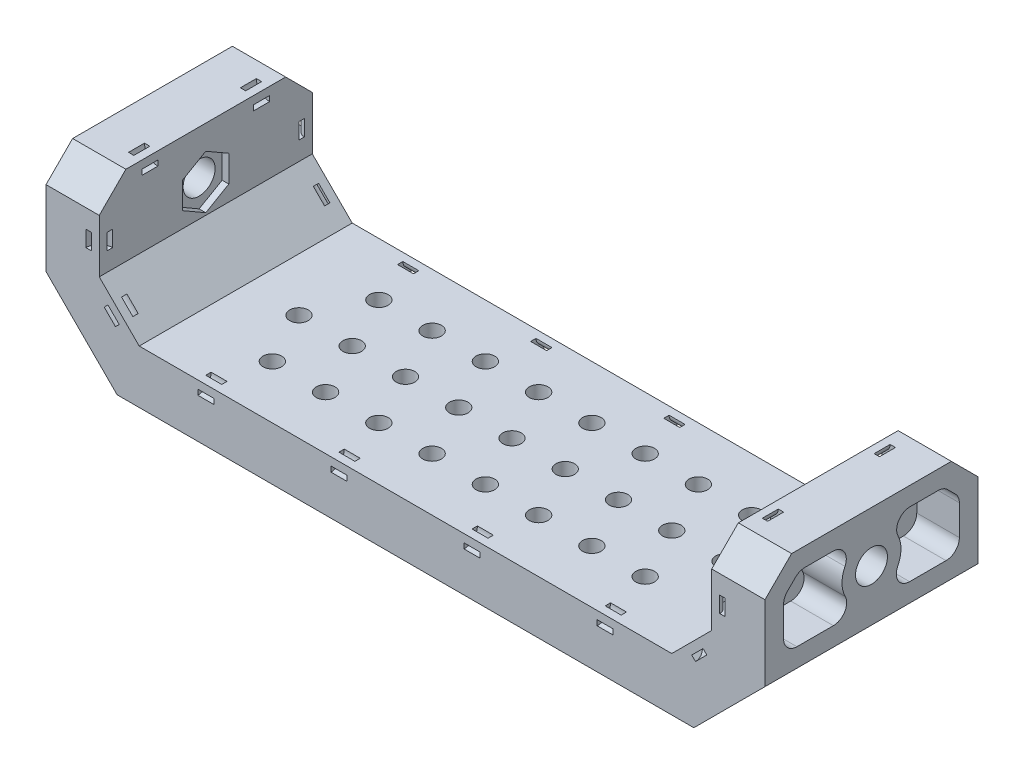
SolidWorks part; units mm, degrees
material "ПК/АБС"
ref_plane "Спереди" through (0, 0, 0) normal (0, 0, 1) x (1, 0, 0)
ref_plane "Сверху" through (0, 0, 0) normal (0, 1, 0) x (1, 0, 0)
ref_plane "Справа" through (0, 0, 0) normal (1, 0, 0) x (0, 0, -1)
sketch "Эскиз1" plane through (0, 0, 0) normal (0, 0, 1) x (1, 0, 0)
  line L0 (0, 47.714) -> (0, -34.8735) construction
  line L1 (-100, 0) -> (100, 0)
  line L2 (100, 0) -> (115, 15)
  line L3 (115, 15) -> (115, 45)
  line L4 (115, 45) -> (135, 45)
  line L5 (-108.2843, -20) -> (108.2843, -20)
  line L6 (108.2843, -20) -> (135, 6.7157)
  line L7 (135, 45) -> (135, 6.7157)
  line L8 (-135, 45) -> (-135, 6.7157)
  line L9 (-108.2843, -20) -> (-135, 6.7157)
  line L10 (-115, 45) -> (-135, 45)
  line L11 (-115, 15) -> (-115, 45)
  line L12 (-100, 0) -> (-115, 15)
  point P14 (0, -20)
  point P17 (0, 0)
  dimension "D1" = 100
  dimension "D2" = 45
  dimension "D3" = 45
  dimension "D4" = 20
  dimension "D5" = 15
  dimension "D6" = 20
  dimension "D7" = 20
extrude "Бобышка-Вытянуть1" add sketch "Эскиз1" along normal blind 40 and the other way blind 40
chamfer "Фаска1" distance 10 angle 45 4 edges at (125, 45, 40) (125, 45, -40) (-125, 45, -40) (-125, 45, 40)
sketch "Эскиз2" plane through (0, 0, 0) normal (0, 1, 0) x (1, 0, 0)
  line L0 (-135, 0) -> (135, 0) construction
  line L1 (-135, 30) -> (-135, -30) construction
  line L2 (135, 30) -> (135, -30) construction
  line L4 (0, 40) -> (0, -40) construction
  line L5 (100, 40) -> (-100, 40) construction
  line L6 (100, -40) -> (-100, -40) construction
  circle A0 centre (0, 0) radius 3.5
  circle A1 centre (20, 0) radius 3.5
  circle A2 centre (40, 0) radius 3.5
  circle A3 centre (60, 0) radius 3.5
  circle A4 centre (80, 0) radius 3.5
  circle A5 centre (0, 0) radius 3.5
  circle A6 centre (20, 0) radius 3.5
  circle A7 centre (40, 0) radius 3.5
  circle A8 centre (60, 0) radius 3.5
  circle A9 centre (-20, 0) radius 3.5
  circle A10 centre (0, 0) radius 3.5
  circle A11 centre (20, 0) radius 3.5
  circle A12 centre (40, 0) radius 3.5
  circle A13 centre (-40, 0) radius 3.5
  circle A14 centre (-20, 0) radius 3.5
  circle A15 centre (0, 0) radius 3.5
  circle A16 centre (20, 0) radius 3.5
  circle A17 centre (-60, 0) radius 3.5
  circle A18 centre (-40, 0) radius 3.5
  circle A19 centre (-20, 0) radius 3.5
  circle A20 centre (0, 0) radius 3.5
  circle A21 centre (-20, 0) radius 3.5
  circle A22 centre (-40, 0) radius 3.5
  circle A23 centre (-60, 0) radius 3.5
  circle A24 centre (-80, 0) radius 3.5
  circle A25 centre (10, -20) radius 3.5
  circle A26 centre (30, -20) radius 3.5
  circle A27 centre (50, -20) radius 3.5
  circle A28 centre (70, -20) radius 3.5
  circle A29 centre (30, 20) radius 3.5
  circle A30 centre (50, 20) radius 3.5
  circle A31 centre (70, 20) radius 3.5
  circle A32 centre (10, 20) radius 3.5
  circle A33 centre (-70, 20) radius 3.5
  circle A34 centre (-50, 20) radius 3.5
  circle A35 centre (-30, 20) radius 3.5
  circle A36 centre (-10, 20) radius 3.5
  circle A37 centre (-10, -20) radius 3.5
  circle A38 centre (-30, -20) radius 3.5
  circle A39 centre (-50, -20) radius 3.5
  circle A40 centre (-70, -20) radius 3.5
  dimension "D1" = 7
  dimension "D2" = 5
  dimension "D3" = 5
  dimension "D4" = 7
  dimension "D5" = 10
  dimension "D6" = 20
  dimension "D7" = 4
  dimension "D8" = 2
extrude "Вырез-Вытянуть3" cut sketch "Эскиз2" against normal blind 30 contours A1 | A2 | A3 | A4 | A28 | A27 | A26 | A25 | A37 | A0 | A38 | A9 | A13 | A17 | A24 | A39 | A40 | A33 | A34 | A35 | A36 | A32 | A29 | A30 | A31 region at (0, 0, 0) region at (20, 0, 0) region at (40, 0, 0) region at (60, 0, 0) region at (80, 0, 0) region at (-20, 0, 0) region at (-40, 0, 0) region at (-60, 0, 0) region at (-80, 0, 0) region at (10, 0, 20) region at (30, 0, 20) region at (50, 0, 20) region at (70, 0, 20) region at (30, 0, -20) region at (50, 0, -20) region at (70, 0, -20) region at (10, 0, -20) region at (-70, 0, -20) region at (-50, 0, -20) region at (-30, 0, -20) region at (-10, 0, -20) region at (-10, 0, 20) region at (-30, 0, 20) region at (-50, 0, 20) region at (-70, 0, 20)
sketch "Эскиз3" plane through (0, -20, 0) normal (0, -1, 0) x (1, 0, 0)
  line L6 (-50.8944, -11.5029) -> (-53.6987, -5.8944) construction
  line L7 (-90.2843, 33) -> (-80.5902, 33)
  line L21 (-71.9098, 3) -> (-68.0902, 3) construction
  line L26 (-71.9098, -3) -> (-68.0902, -3) construction
  line L27 (-69.1056, -11.5029) -> (-66.3013, -5.8944) construction
  line L40 (0, 0) -> (-150.2683, 0) construction
  line L52 (-67.3541, 32) -> (-69.1056, 28.4971) construction
  line L53 (-75.1355, 25.7989) -> (-77.9069, 31.3416)
  line L66 (-72.6459, -32) -> (-70.8944, -28.4971) construction
  line L81 (-60.8944, 8.4971) -> (-63.9701, 14.6484) construction
  line L82 (-60.8944, 31.5029) -> (-63.9701, 25.3516) construction
  line L97 (-73.6987, -5.8944) -> (-70.8944, -11.5029) construction
  line L113 (-66.3013, 5.8944) -> (-69.1056, 11.5029) construction
  line L114 (-46.3013, -5.8944) -> (-49.1056, -11.5029) construction
  line L129 (-69.1056, -28.4971) -> (-67.3541, -32) construction
  line L130 (-70.8944, 28.4971) -> (-72.6459, 32) construction
  line L162 (-75.1355, 14.2011) -> (-78.4422, 7.5877)
  line L165 (-98.2843, 2) -> (-87.4833, 2)
  line L166 (-70.8944, 11.5029) -> (-73.6987, 5.8944) construction
  line L167 (-72.6459, 32) -> (-67.3541, 32) construction
  line L168 (-51.9098, -3) -> (-48.0902, -3) construction
  line L169 (-72.6459, -32) -> (-67.3541, -32) construction
  line L170 (-52.6459, -32) -> (-47.3541, -32) construction
  line L171 (-51.9098, 3) -> (-48.0902, 3) construction
  line L172 (-47.3541, 32) -> (-49.1056, 28.4971) construction
  line L173 (-50.8944, -28.4971) -> (-52.6459, -32) construction
  line L174 (-47.3541, -32) -> (-49.1056, -28.4971) construction
  line L175 (-46.3013, 5.8944) -> (-49.1056, 11.5029) construction
  line L176 (-50.8944, 28.4971) -> (-52.6459, 32) construction
  line L177 (-56.0299, 14.6484) -> (-59.1056, 8.4971) construction
  line L178 (-56.0299, 25.3516) -> (-59.1056, 31.5029) construction
  line L179 (-50.8944, 11.5029) -> (-53.6987, 5.8944) construction
  line L180 (-52.6459, 32) -> (-47.3541, 32) construction
  line L181 (-56.0299, -14.6484) -> (-59.1056, -8.4971) construction
  line L182 (-56.0299, -25.3516) -> (-59.1056, -31.5029) construction
  line L183 (-60.8944, -31.5029) -> (-63.9701, -25.3516) construction
  line L184 (-60.8944, -8.4971) -> (-63.9701, -14.6484) construction
  line L185 (-40.8944, 8.4971) -> (-43.9701, 14.6484) construction
  line L186 (-40.8944, 31.5029) -> (-43.9701, 25.3516) construction
  line L187 (-36.0299, 25.3516) -> (-39.1056, 31.5029) construction
  line L188 (-36.0299, 14.6484) -> (-39.1056, 8.4971) construction
  line L189 (-27.3541, 32) -> (-29.1056, 28.4971) construction
  line L190 (-30.8944, 28.4971) -> (-32.6459, 32) construction
  line L191 (-32.6459, 32) -> (-27.3541, 32) construction
  line L192 (-31.9098, 3) -> (-28.0902, 3) construction
  line L193 (-26.3013, 5.8944) -> (-29.1056, 11.5029) construction
  line L194 (-30.8944, 11.5029) -> (-33.6987, 5.8944) construction
  line L195 (-31.9098, -3) -> (-28.0902, -3) construction
  line L196 (-26.3013, -5.8944) -> (-29.1056, -11.5029) construction
  line L197 (-30.8944, -11.5029) -> (-33.6987, -5.8944) construction
  line L198 (-32.6459, -32) -> (-27.3541, -32) construction
  line L199 (-27.3541, -32) -> (-29.1056, -28.4971) construction
  line L260 (-101.2843, 22) -> (-101.2843, 5)
  line L261 (-71.7889, 28.0498) -> (-74.2639, 33)
  line L262 (-74.2639, 33) -> (-65.7361, 33)
  line L263 (-30.8944, -28.4971) -> (-32.6459, -32) construction
  line L264 (-36.0299, -14.6484) -> (-39.1056, -8.4971) construction
  line L265 (-40.8944, -8.4971) -> (-43.9701, -14.6484) construction
  line L266 (-40.8944, -31.5029) -> (-43.9701, -25.3516) construction
  line L267 (-36.0299, -25.3516) -> (-39.1056, -31.5029) construction
  line L268 (-20.8944, 8.4971) -> (-23.9701, 14.6484) construction
  line L269 (-20.8944, 31.5029) -> (-23.9701, 25.3516) construction
  line L270 (-16.0299, 25.3516) -> (-19.1056, 31.5029) construction
  line L271 (-16.0299, 14.6484) -> (-19.1056, 8.4971) construction
  line L272 (-7.3541, 32) -> (-9.1056, 28.4971) construction
  line L273 (-10.8944, 28.4971) -> (-12.6459, 32) construction
  line L274 (-12.6459, 32) -> (-7.3541, 32) construction
  line L275 (-11.9098, 3) -> (-8.0902, 3) construction
  line L276 (-6.3013, 5.8944) -> (-9.1056, 11.5029) construction
  line L277 (-10.8944, 11.5029) -> (-13.6987, 5.8944) construction
  line L278 (-11.9098, -3) -> (-8.0902, -3) construction
  line L279 (-6.3013, -5.8944) -> (-9.1056, -11.5029) construction
  line L280 (-10.8944, -11.5029) -> (-13.6987, -5.8944) construction
  line L281 (-12.6459, -32) -> (-7.3541, -32) construction
  line L282 (-7.3541, -32) -> (-9.1056, -28.4971) construction
  line L283 (-10.8944, -28.4971) -> (-12.6459, -32) construction
  line L284 (-16.0299, -14.6484) -> (-19.1056, -8.4971) construction
  line L285 (-20.8944, -8.4971) -> (-23.9701, -14.6484) construction
  line L286 (-20.8944, -31.5029) -> (-23.9701, -25.3516) construction
  line L287 (-16.0299, -25.3516) -> (-19.1056, -31.5029) construction
  line L288 (-0.8944, 8.4971) -> (-3.9701, 14.6484) construction
  line L289 (-0.8944, 31.5029) -> (-3.9701, 25.3516) construction
  line L290 (3.9701, 25.3516) -> (0.8944, 31.5029) construction
  line L291 (3.9701, 14.6484) -> (0.8944, 8.4971) construction
  line L292 (12.6459, 32) -> (10.8944, 28.4971) construction
  line L293 (9.1056, 28.4971) -> (7.3541, 32) construction
  line L294 (7.3541, 32) -> (12.6459, 32) construction
  line L295 (8.0902, 3) -> (11.9098, 3) construction
  line L296 (13.6987, 5.8944) -> (10.8944, 11.5029) construction
  line L297 (9.1056, 11.5029) -> (6.3013, 5.8944) construction
  line L298 (8.0902, -3) -> (11.9098, -3) construction
  line L299 (13.6987, -5.8944) -> (10.8944, -11.5029) construction
  line L300 (9.1056, -11.5029) -> (6.3013, -5.8944) construction
  line L301 (7.3541, -32) -> (12.6459, -32) construction
  line L302 (12.6459, -32) -> (10.8944, -28.4971) construction
  line L303 (9.1056, -28.4971) -> (7.3541, -32) construction
  line L304 (3.9701, -14.6484) -> (0.8944, -8.4971) construction
  line L305 (-0.8944, -8.4971) -> (-3.9701, -14.6484) construction
  line L306 (-0.8944, -31.5029) -> (-3.9701, -25.3516) construction
  line L307 (3.9701, -25.3516) -> (0.8944, -31.5029) construction
  line L308 (19.1056, 8.4971) -> (16.0299, 14.6484) construction
  line L309 (19.1056, 31.5029) -> (16.0299, 25.3516) construction
  line L310 (23.9701, 25.3516) -> (20.8944, 31.5029) construction
  line L311 (23.9701, 14.6484) -> (20.8944, 8.4971) construction
  line L312 (32.6459, 32) -> (30.8944, 28.4971) construction
  line L313 (29.1056, 28.4971) -> (27.3541, 32) construction
  line L314 (27.3541, 32) -> (32.6459, 32) construction
  line L315 (28.0902, 3) -> (31.9098, 3) construction
  line L316 (33.6987, 5.8944) -> (30.8944, 11.5029) construction
  line L317 (29.1056, 11.5029) -> (26.3013, 5.8944) construction
  line L318 (28.0902, -3) -> (31.9098, -3) construction
  line L319 (33.6987, -5.8944) -> (30.8944, -11.5029) construction
  line L320 (29.1056, -11.5029) -> (26.3013, -5.8944) construction
  line L321 (27.3541, -32) -> (32.6459, -32) construction
  line L322 (32.6459, -32) -> (30.8944, -28.4971) construction
  line L323 (29.1056, -28.4971) -> (27.3541, -32) construction
  line L324 (23.9701, -14.6484) -> (20.8944, -8.4971) construction
  line L325 (19.1056, -8.4971) -> (16.0299, -14.6484) construction
  line L326 (19.1056, -31.5029) -> (16.0299, -25.3516) construction
  line L327 (23.9701, -25.3516) -> (20.8944, -31.5029) construction
  line L328 (39.1056, 8.4971) -> (36.0299, 14.6484) construction
  line L329 (39.1056, 31.5029) -> (36.0299, 25.3516) construction
  line L330 (43.9701, 25.3516) -> (40.8944, 31.5029) construction
  line L331 (43.9701, 14.6484) -> (40.8944, 8.4971) construction
  line L332 (52.6459, 32) -> (50.8944, 28.4971) construction
  line L333 (49.1056, 28.4971) -> (47.3541, 32) construction
  line L334 (47.3541, 32) -> (52.6459, 32) construction
  line L335 (48.0902, 3) -> (51.9098, 3) construction
  line L336 (53.6987, 5.8944) -> (50.8944, 11.5029) construction
  line L337 (49.1056, 11.5029) -> (46.3013, 5.8944) construction
  line L338 (48.0902, -3) -> (51.9098, -3) construction
  line L339 (53.6987, -5.8944) -> (50.8944, -11.5029) construction
  line L340 (49.1056, -11.5029) -> (46.3013, -5.8944) construction
  line L341 (-65.7361, 33) -> (-68.2111, 28.0498)
  line L342 (-61.7889, 31.9502) -> (-64.8645, 25.7989)
  line L343 (-40.6634, 8.0349) -> (-43.9701, 14.6484) [skipped]
  line L344 (-41.1987, 30.8944) -> (-43.9701, 25.3516) [skipped]
  line L345 (47.3541, -32) -> (52.6459, -32) construction
  line L346 (52.6459, -32) -> (50.8944, -28.4971) construction
  line L347 (49.1056, -28.4971) -> (47.3541, -32) construction
  line L348 (43.9701, -14.6484) -> (40.8944, -8.4971) construction
  line L349 (39.1056, -8.4971) -> (36.0299, -14.6484) construction
  line L350 (39.1056, -31.5029) -> (36.0299, -25.3516) construction
  line L351 (43.9701, -25.3516) -> (40.8944, -31.5029) construction
  line L352 (59.1056, 8.4971) -> (56.0299, 14.6484) construction
  line L353 (59.1056, 31.5029) -> (56.0299, 25.3516) construction
  line L354 (63.9701, 25.3516) -> (60.8944, 31.5029) construction
  line L355 (63.9701, 14.6484) -> (60.8944, 8.4971) construction
  line L356 (72.6459, 32) -> (70.8944, 28.4971) construction
  line L357 (69.1056, 28.4971) -> (67.3541, 32) construction
  line L358 (67.3541, 32) -> (72.6459, 32) construction
  line L359 (68.0902, 3) -> (71.9098, 3) construction
  line L360 (73.6987, 5.8944) -> (70.8944, 11.5029) construction
  line L361 (69.1056, 11.5029) -> (66.3013, 5.8944) construction
  line L362 (68.0902, -3) -> (71.9098, -3) construction
  line L363 (73.6987, -5.8944) -> (70.8944, -11.5029) construction
  line L364 (69.1056, -11.5029) -> (66.3013, -5.8944) construction
  line L365 (67.3541, -32) -> (72.6459, -32) construction
  line L366 (72.6459, -32) -> (70.8944, -28.4971) construction
  line L367 (69.1056, -28.4971) -> (67.3541, -32) construction
  line L368 (63.9701, -14.6484) -> (60.8944, -8.4971) construction
  line L369 (59.1056, -8.4971) -> (56.0299, -14.6484) construction
  line L370 (59.1056, -31.5029) -> (56.0299, -25.3516) construction
  line L371 (63.9701, -25.3516) -> (60.8944, -31.5029) construction
  line L372 (0, 0) -> (0, 61.0557) construction
  line L373 (98.2843, -3) -> (87.4833, -3) construction
  line L374 (100.2843, -5) -> (100.2843, -22) construction
  line L375 (90.2843, -32) -> (79.3541, -32) construction
  line L376 (79.3541, -32) -> (76.0299, -25.3516) construction
  line L377 (79.3366, -8.0349) -> (76.0299, -14.6484) construction
  line L383 (-61.7889, 8.0498) -> (-64.8645, 14.2011)
  line L384 (-55.1355, 14.2011) -> (-58.2111, 8.0498)
  line L385 (-55.1355, 25.7989) -> (-58.2111, 31.9502)
  line L386 (-71.7889, 11.9502) -> (-74.5931, 6.3416)
  line L387 (-71.9098, 2) -> (-68.0902, 2)
  line L388 (-65.4069, 6.3416) -> (-68.2111, 11.9502)
  line L389 (-78.4422, -7.5877) -> (-75.1355, -14.2011)
  line L390 (-78.7361, -33) -> (-75.1355, -25.7989)
  line L391 (-90.2843, -33) -> (-78.7361, -33)
  line L392 (-101.2843, -5) -> (-101.2843, -22)
  line L393 (-98.2843, -2) -> (-87.4833, -2)
  line L394 (-74.5931, -6.3416) -> (-71.7889, -11.9502)
  line L395 (-68.2111, -11.9502) -> (-65.4069, -6.3416)
  line L396 (-71.9098, -2) -> (-68.0902, -2)
  line L397 (-61.7889, -8.0498) -> (-64.8645, -14.2011)
  line L398 (-61.7889, -31.9502) -> (-64.8645, -25.7989)
  line L399 (-55.1355, -25.7989) -> (-58.2111, -31.9502)
  line L400 (-55.1355, -14.2011) -> (-58.2111, -8.0498)
  line L401 (-68.2111, -28.0498) -> (-65.7361, -33)
  line L402 (-74.2639, -33) -> (-65.7361, -33)
  line L403 (-74.2639, -33) -> (-71.7889, -28.0498)
  line L404 (-51.7889, -28.0498) -> (-54.2639, -33)
  line L405 (-54.2639, -33) -> (-45.7361, -33)
  line L406 (-45.7361, -33) -> (-48.2111, -28.0498)
  line L407 (-51.7889, -11.9502) -> (-54.5931, -6.3416)
  line L408 (-51.9098, -2) -> (-48.0902, -2)
  line L409 (-45.4069, -6.3416) -> (-48.2111, -11.9502)
  line L410 (-51.7889, 11.9502) -> (-54.5931, 6.3416)
  line L411 (-51.9098, 2) -> (-48.0902, 2)
  line L412 (-45.4069, 6.3416) -> (-48.2111, 11.9502)
  line L413 (-51.7889, 28.0498) -> (-54.2639, 33)
  line L414 (-54.2639, 33) -> (-45.7361, 33)
  line L415 (-45.7361, 33) -> (-48.2111, 28.0498)
  line L416 (-41.7889, 31.9502) -> (-44.8645, 25.7989)
  line L417 (-41.7889, 8.0498) -> (-44.8645, 14.2011)
  line L418 (-35.1355, 14.2011) -> (-38.2111, 8.0498)
  line L419 (-35.1355, 25.7989) -> (-38.2111, 31.9502)
  line L420 (-31.7889, 28.0498) -> (-34.2639, 33)
  line L421 (-34.2639, 33) -> (-25.7361, 33)
  line L422 (-25.7361, 33) -> (-28.2111, 28.0498)
  line L423 (-21.7889, 31.9502) -> (-24.8645, 25.7989)
  line L424 (-21.7889, 8.0498) -> (-24.8645, 14.2011)
  line L425 (-15.1355, 14.2011) -> (-18.2111, 8.0498)
  line L426 (-15.1355, 25.7989) -> (-18.2111, 31.9502)
  line L427 (-25.4069, 6.3416) -> (-28.2111, 11.9502)
  line L428 (-31.7889, 11.9502) -> (-34.5931, 6.3416)
  line L429 (-31.9098, 2) -> (-28.0902, 2)
  line L430 (-31.7889, -11.9502) -> (-34.5931, -6.3416)
  line L431 (-31.9098, -2) -> (-28.0902, -2)
  line L432 (-25.4069, -6.3416) -> (-28.2111, -11.9502)
  line L433 (-35.1355, -14.2011) -> (-38.2111, -8.0498)
  line L434 (-41.7889, -8.0498) -> (-44.8645, -14.2011)
  line L435 (-41.7889, -31.9502) -> (-44.8645, -25.7989)
  line L436 (-35.1355, -25.7989) -> (-38.2111, -31.9502)
  line L437 (-31.7889, -28.0498) -> (-34.2639, -33)
  line L438 (-34.2639, -33) -> (-25.7361, -33)
  line L439 (-25.7361, -33) -> (-28.2111, -28.0498)
  line L440 (-21.7889, -31.9502) -> (-24.8645, -25.7989)
  line L441 (-15.1355, -25.7989) -> (-18.2111, -31.9502)
  line L442 (-15.1355, -14.2011) -> (-18.2111, -8.0498)
  line L443 (-21.7889, -8.0498) -> (-24.8645, -14.2011)
  line L444 (-11.7889, 11.9502) -> (-14.5931, 6.3416)
  line L445 (-11.9098, 2) -> (-8.0902, 2)
  line L446 (-5.4069, 6.3416) -> (-8.2111, 11.9502)
  line L447 (-11.7889, -11.9502) -> (-14.5931, -6.3416)
  line L448 (-11.9098, -2) -> (-8.0902, -2)
  line L449 (-5.4069, -6.3416) -> (-8.2111, -11.9502)
  line L450 (-11.7889, -28.0498) -> (-14.2639, -33)
  line L451 (-14.2639, -33) -> (-5.7361, -33)
  line L452 (-5.7361, -33) -> (-8.2111, -28.0498)
  line L453 (-11.7889, 28.0498) -> (-14.2639, 33)
  line L454 (-14.2639, 33) -> (-5.7361, 33)
  line L455 (-5.7361, 33) -> (-8.2111, 28.0498)
  line L456 (-1.7889, 31.9502) -> (-4.8645, 25.7989)
  line L457 (-1.7889, 8.0498) -> (-4.8645, 14.2011)
  line L458 (4.8645, 14.2011) -> (1.7889, 8.0498)
  line L459 (4.8645, 25.7989) -> (1.7889, 31.9502)
  line L460 (8.2111, 28.0498) -> (5.7361, 33)
  line L461 (5.7361, 33) -> (14.2639, 33)
  line L462 (14.2639, 33) -> (11.7889, 28.0498)
  line L463 (8.2111, 11.9502) -> (5.4069, 6.3416)
  line L464 (8.0902, 2) -> (11.9098, 2)
  line L465 (14.5931, 6.3416) -> (11.7889, 11.9502)
  line L466 (8.2111, -11.9502) -> (5.4069, -6.3416)
  line L467 (8.0902, -2) -> (11.9098, -2)
  line L468 (14.5931, -6.3416) -> (11.7889, -11.9502)
  line L469 (4.8645, -14.2011) -> (1.7889, -8.0498)
  line L470 (-1.7889, -8.0498) -> (-4.8645, -14.2011)
  line L471 (-1.7889, -31.9502) -> (-4.8645, -25.7989)
  line L472 (4.8645, -25.7989) -> (1.7889, -31.9502)
  line L473 (8.2111, -28.0498) -> (5.7361, -33)
  line L474 (5.7361, -33) -> (14.2639, -33)
  line L475 (14.2639, -33) -> (11.7889, -28.0498)
  line L476 (18.2111, -8.0498) -> (15.1355, -14.2011)
  line L477 (18.2111, -31.9502) -> (15.1355, -25.7989)
  line L478 (24.8645, -25.7989) -> (21.7889, -31.9502)
  line L479 (24.8645, -14.2011) -> (21.7889, -8.0498)
  line L480 (18.2111, 31.9502) -> (15.1355, 25.7989)
  line L481 (18.2111, 8.0498) -> (15.1355, 14.2011)
  line L482 (24.8645, 14.2011) -> (21.7889, 8.0498)
  line L483 (24.8645, 25.7989) -> (21.7889, 31.9502)
  line L484 (28.2111, 28.0498) -> (25.7361, 33)
  line L485 (25.7361, 33) -> (34.2639, 33)
  line L486 (34.2639, 33) -> (31.7889, 28.0498)
  line L487 (28.2111, 11.9502) -> (25.4069, 6.3416)
  line L488 (28.0902, 2) -> (31.9098, 2)
  line L489 (34.5931, 6.3416) -> (31.7889, 11.9502)
  line L490 (28.2111, -11.9502) -> (25.4069, -6.3416)
  line L491 (28.0902, -2) -> (31.9098, -2)
  line L492 (34.5931, -6.3416) -> (31.7889, -11.9502)
  line L493 (28.2111, -28.0498) -> (25.7361, -33)
  line L494 (25.7361, -33) -> (34.2639, -33)
  line L495 (34.2639, -33) -> (31.7889, -28.0498)
  line L496 (38.2111, -31.9502) -> (35.1355, -25.7989)
  line L497 (38.2111, -8.0498) -> (35.1355, -14.2011)
  line L498 (44.8645, -14.2011) -> (41.7889, -8.0498)
  line L499 (44.8645, -25.7989) -> (41.7889, -31.9502)
  line L500 (48.2111, -28.0498) -> (45.7361, -33)
  line L501 (45.7361, -33) -> (54.2639, -33)
  line L502 (54.2639, -33) -> (51.7889, -28.0498)
  line L503 (58.2111, -31.9502) -> (55.1355, -25.7989)
  line L504 (58.2111, -8.0498) -> (55.1355, -14.2011)
  line L505 (64.8645, -14.2011) -> (61.7889, -8.0498)
  line L506 (64.8645, -25.7989) -> (61.7889, -31.9502)
  line L507 (68.2111, -28.0498) -> (65.7361, -33)
  line L508 (65.7361, -33) -> (74.2639, -33)
  line L509 (74.2639, -33) -> (71.7889, -28.0498)
  line L510 (68.2111, -11.9502) -> (65.4069, -6.3416)
  line L511 (68.0902, -2) -> (71.9098, -2)
  line L512 (74.5931, -6.3416) -> (71.7889, -11.9502)
  line L513 (54.5931, -6.3416) -> (51.7889, -11.9502)
  line L514 (48.2111, -11.9502) -> (45.4069, -6.3416)
  line L515 (48.0902, -2) -> (51.9098, -2)
  line L516 (48.2111, 11.9502) -> (45.4069, 6.3416)
  line L517 (48.0902, 2) -> (51.9098, 2)
  line L518 (54.5931, 6.3416) -> (51.7889, 11.9502)
  line L519 (44.8645, 14.2011) -> (41.7889, 8.0498)
  line L520 (38.2111, 8.0498) -> (35.1355, 14.2011)
  line L521 (38.2111, 31.9502) -> (35.1355, 25.7989)
  line L522 (44.8645, 25.7989) -> (41.7889, 31.9502)
  line L523 (48.2111, 28.0498) -> (45.7361, 33)
  line L524 (45.7361, 33) -> (54.2639, 33)
  line L525 (54.2639, 33) -> (51.7889, 28.0498)
  line L526 (64.8645, 25.7989) -> (61.7889, 31.9502)
  line L527 (58.2111, 31.9502) -> (55.1355, 25.7989)
  line L528 (58.2111, 8.0498) -> (55.1355, 14.2011)
  line L529 (64.8645, 14.2011) -> (61.7889, 8.0498)
  line L530 (74.2639, 33) -> (71.7889, 28.0498)
  line L531 (68.2111, 28.0498) -> (65.7361, 33)
  line L532 (65.7361, 33) -> (74.2639, 33)
  line L533 (74.5931, 6.3416) -> (71.7889, 11.9502)
  line L534 (68.2111, 11.9502) -> (65.4069, 6.3416)
  line L535 (68.0902, 2) -> (71.9098, 2)
  line L536 (75.1355, 14.2011) -> (78.4422, 7.5877)
  line L537 (98.2843, 2) -> (87.4833, 2)
  line L538 (101.2843, 22) -> (101.2843, 5)
  line L539 (90.2843, 33) -> (80.5902, 33)
  line L540 (75.1355, 25.7989) -> (77.9069, 31.3416)
  line L541 (78.4422, -7.5877) -> (75.1355, -14.2011)
  line L542 (78.7361, -33) -> (75.1355, -25.7989)
  line L543 (90.2843, -33) -> (78.7361, -33)
  line L544 (101.2843, -5) -> (101.2843, -22)
  line L545 (98.2843, -2) -> (87.4833, -2)
  arc A45 (-59.1056, 8.4971) -> (-60.8944, 8.4971) centre (-60, 8.9443) cw construction
  arc A50 (-63.9187, 16.5333) -> (-63.9187, 23.4667) centre (-70, 20) ccw construction
  arc A51 (-53.6987, -5.8944) -> (-51.9098, -3) centre (-51.9098, -5) cw construction
  arc A55 (-49.1056, -11.5029) -> (-50.8944, -11.5029) centre (-50, -11.0557) cw construction
  arc A56 (-48.0902, -3) -> (-46.3013, -5.8944) centre (-48.0902, -5) cw construction
  arc A57 (-49.1056, -28.4971) -> (-50.8944, -28.4971) centre (-50, -28.9443) ccw construction
  arc A145 (-59.1056, 31.5029) -> (-60.8944, 31.5029) centre (-60, 31.0557) ccw construction
  arc A146 (-101.2843, 22) -> (-90.2843, 33) centre (-90.2843, 22) cw
  arc A180 (-77.9069, 31.3416) -> (-80.5902, 33) centre (-80.5902, 30) ccw
  arc A182 (-66.3013, -5.8944) -> (-68.0902, -3) centre (-68.0902, -5) ccw construction
  arc A183 (-73.6987, -5.8944) -> (-71.9098, -3) centre (-71.9098, -5) cw construction
  arc A184 (-73.6987, 5.8944) -> (-71.9098, 3) centre (-71.9098, 5) ccw construction
  arc A185 (-68.0902, 3) -> (-66.3013, 5.8944) centre (-68.0902, 5) ccw construction
  arc A186 (-56.0299, -14.6484) -> (-56.0813, -16.5333) centre (-57.8188, -15.5428) cw construction
  arc A187 (-63.9701, 14.6484) -> (-63.9187, 16.5333) centre (-62.1812, 15.5428) cw construction
  arc A188 (-63.9187, 23.4667) -> (-63.9701, 25.3516) centre (-62.1812, 24.4572) cw construction
  arc A189 (-56.0813, -23.4667) -> (-56.0813, -16.5333) centre (-50, -20) cw construction
  arc A195 (-69.1056, -28.4971) -> (-70.8944, -28.4971) centre (-70, -28.9443) ccw construction
  arc A196 (-69.1056, 28.4971) -> (-70.8944, 28.4971) centre (-70, 28.9443) cw construction
  arc A197 (-69.1056, -11.5029) -> (-70.8944, -11.5029) centre (-70, -11.0557) cw construction
  arc A198 (-69.1056, 11.5029) -> (-70.8944, 11.5029) centre (-70, 11.0557) ccw construction
  arc A199 (-56.0813, 23.4667) -> (-56.0813, 16.5333) centre (-50, 20) ccw construction
  arc A200 (-56.0813, -23.4667) -> (-56.0299, -25.3516) centre (-57.8188, -24.4572) cw construction
  arc A201 (-53.6987, 5.8944) -> (-51.9098, 3) centre (-51.9098, 5) ccw construction
  arc A202 (-48.0902, 3) -> (-46.3013, 5.8944) centre (-48.0902, 5) ccw construction
  arc A203 (-59.1056, -31.5029) -> (-60.8944, -31.5029) centre (-60, -31.0557) cw construction
  arc A204 (-63.9187, -23.4667) -> (-63.9701, -25.3516) centre (-62.1812, -24.4572) ccw construction
  arc A205 (-63.9187, -16.5333) -> (-63.9187, -23.4667) centre (-70, -20) cw construction
  arc A206 (-75.2125, 22.9715) -> (-75.1355, 25.7989) centre (-77.8188, 24.4572) ccw
  arc A207 (-63.9701, -14.6484) -> (-63.9187, -16.5333) centre (-62.1812, -15.5428) ccw construction
  arc A208 (-59.1056, -8.4971) -> (-60.8944, -8.4971) centre (-60, -8.9443) ccw construction
  arc A329 (-75.2125, 22.9715) -> (-75.2125, 17.0285) centre (-70, 20) ccw
  arc A330 (-75.1355, 14.2011) -> (-75.2125, 17.0285) centre (-77.8188, 15.5428) ccw
  arc A331 (-56.0299, 14.6484) -> (-56.0813, 16.5333) centre (-57.8188, 15.5428) ccw construction
  arc A332 (-56.0813, 23.4667) -> (-56.0299, 25.3516) centre (-57.8188, 24.4572) ccw construction
  arc A333 (-39.1056, 8.4971) -> (-40.8944, 8.4971) centre (-40, 8.9443) cw construction
  arc A334 (-80.7503, 5.9529) -> (-78.4422, 7.5877) centre (-81.1255, 8.9293) ccw
  arc A335 (-49.1056, 28.4971) -> (-50.8944, 28.4971) centre (-50, 28.9443) cw construction
  arc A336 (-49.1056, 11.5029) -> (-50.8944, 11.5029) centre (-50, 11.0557) ccw construction
  arc A337 (-43.9701, 14.6484) -> (-43.9187, 16.5333) centre (-42.1812, 15.5428) cw construction
  arc A338 (-43.9187, 16.5333) -> (-43.9187, 23.4667) centre (-50, 20) ccw construction
  arc A339 (-43.9187, 23.4667) -> (-43.9701, 25.3516) centre (-42.1812, 24.4572) cw construction
  arc A340 (-39.1056, 31.5029) -> (-40.8944, 31.5029) centre (-40, 31.0557) ccw construction
  arc A341 (-36.0813, 23.4667) -> (-36.0299, 25.3516) centre (-37.8188, 24.4572) ccw construction
  arc A342 (-36.0813, 23.4667) -> (-36.0813, 16.5333) centre (-30, 20) ccw construction
  arc A343 (-36.0299, 14.6484) -> (-36.0813, 16.5333) centre (-37.8188, 15.5428) ccw construction
  arc A344 (-29.1056, 28.4971) -> (-30.8944, 28.4971) centre (-30, 28.9443) cw construction
  arc A345 (-28.0902, 3) -> (-26.3013, 5.8944) centre (-28.0902, 5) ccw construction
  arc A346 (-29.1056, 11.5029) -> (-30.8944, 11.5029) centre (-30, 11.0557) ccw construction
  arc A347 (-33.6987, 5.8944) -> (-31.9098, 3) centre (-31.9098, 5) ccw construction
  arc A348 (-33.6987, -5.8944) -> (-31.9098, -3) centre (-31.9098, -5) cw construction
  arc A349 (-28.0902, -3) -> (-26.3013, -5.8944) centre (-28.0902, -5) cw construction
  arc A350 (-29.1056, -11.5029) -> (-30.8944, -11.5029) centre (-30, -11.0557) cw construction
  arc A351 (-29.1056, -28.4971) -> (-30.8944, -28.4971) centre (-30, -28.9443) ccw construction
  arc A352 (-39.1056, -8.4971) -> (-40.8944, -8.4971) centre (-40, -8.9443) ccw construction
  arc A353 (-43.9701, -14.6484) -> (-43.9187, -16.5333) centre (-42.1812, -15.5428) ccw construction
  arc A354 (-43.9187, -16.5333) -> (-43.9187, -23.4667) centre (-50, -20) cw construction
  arc A355 (-43.9187, -23.4667) -> (-43.9701, -25.3516) centre (-42.1812, -24.4572) ccw construction
  arc A356 (-39.1056, -31.5029) -> (-40.8944, -31.5029) centre (-40, -31.0557) cw construction
  arc A357 (-36.0813, -23.4667) -> (-36.0299, -25.3516) centre (-37.8188, -24.4572) cw construction
  arc A358 (-36.0813, -23.4667) -> (-36.0813, -16.5333) centre (-30, -20) cw construction
  arc A359 (-36.0299, -14.6484) -> (-36.0813, -16.5333) centre (-37.8188, -15.5428) cw construction
  arc A360 (-19.1056, 8.4971) -> (-20.8944, 8.4971) centre (-20, 8.9443) cw construction
  arc A361 (-23.9701, 14.6484) -> (-23.9187, 16.5333) centre (-22.1812, 15.5428) cw construction
  arc A362 (-23.9187, 16.5333) -> (-23.9187, 23.4667) centre (-30, 20) ccw construction
  arc A363 (-23.9187, 23.4667) -> (-23.9701, 25.3516) centre (-22.1812, 24.4572) cw construction
  arc A364 (-19.1056, 31.5029) -> (-20.8944, 31.5029) centre (-20, 31.0557) ccw construction
  arc A365 (-16.0813, 23.4667) -> (-16.0299, 25.3516) centre (-17.8188, 24.4572) ccw construction
  arc A366 (-16.0813, 23.4667) -> (-16.0813, 16.5333) centre (-10, 20) ccw construction
  arc A367 (-16.0299, 14.6484) -> (-16.0813, 16.5333) centre (-17.8188, 15.5428) ccw construction
  arc A368 (-9.1056, 28.4971) -> (-10.8944, 28.4971) centre (-10, 28.9443) cw construction
  arc A369 (-8.0902, 3) -> (-6.3013, 5.8944) centre (-8.0902, 5) ccw construction
  arc A370 (-9.1056, 11.5029) -> (-10.8944, 11.5029) centre (-10, 11.0557) ccw construction
  arc A371 (-13.6987, 5.8944) -> (-11.9098, 3) centre (-11.9098, 5) ccw construction
  arc A372 (-13.6987, -5.8944) -> (-11.9098, -3) centre (-11.9098, -5) cw construction
  arc A373 (-8.0902, -3) -> (-6.3013, -5.8944) centre (-8.0902, -5) cw construction
  arc A374 (-9.1056, -11.5029) -> (-10.8944, -11.5029) centre (-10, -11.0557) cw construction
  arc A375 (-9.1056, -28.4971) -> (-10.8944, -28.4971) centre (-10, -28.9443) ccw construction
  arc A376 (-19.1056, -8.4971) -> (-20.8944, -8.4971) centre (-20, -8.9443) ccw construction
  arc A377 (-23.9701, -14.6484) -> (-23.9187, -16.5333) centre (-22.1812, -15.5428) ccw construction
  arc A378 (-23.9187, -16.5333) -> (-23.9187, -23.4667) centre (-30, -20) cw construction
  arc A379 (-23.9187, -23.4667) -> (-23.9701, -25.3516) centre (-22.1812, -24.4572) ccw construction
  arc A380 (-19.1056, -31.5029) -> (-20.8944, -31.5029) centre (-20, -31.0557) cw construction
  arc A381 (-16.0813, -23.4667) -> (-16.0299, -25.3516) centre (-17.8188, -24.4572) cw construction
  arc A382 (-16.0813, -23.4667) -> (-16.0813, -16.5333) centre (-10, -20) cw construction
  arc A383 (-16.0299, -14.6484) -> (-16.0813, -16.5333) centre (-17.8188, -15.5428) cw construction
  arc A384 (0.8944, 8.4971) -> (-0.8944, 8.4971) centre (0, 8.9443) cw construction
  arc A385 (-3.9701, 14.6484) -> (-3.9187, 16.5333) centre (-2.1812, 15.5428) cw construction
  arc A386 (-3.9187, 16.5333) -> (-3.9187, 23.4667) centre (-10, 20) ccw construction
  arc A387 (-3.9187, 23.4667) -> (-3.9701, 25.3516) centre (-2.1812, 24.4572) cw construction
  arc A388 (0.8944, 31.5029) -> (-0.8944, 31.5029) centre (0, 31.0557) ccw construction
  arc A389 (3.9187, 23.4667) -> (3.9701, 25.3516) centre (2.1812, 24.4572) ccw construction
  arc A390 (3.9187, 23.4667) -> (3.9187, 16.5333) centre (10, 20) ccw construction
  arc A391 (3.9701, 14.6484) -> (3.9187, 16.5333) centre (2.1812, 15.5428) ccw construction
  arc A392 (10.8944, 28.4971) -> (9.1056, 28.4971) centre (10, 28.9443) cw construction
  arc A393 (11.9098, 3) -> (13.6987, 5.8944) centre (11.9098, 5) ccw construction
  arc A394 (10.8944, 11.5029) -> (9.1056, 11.5029) centre (10, 11.0557) ccw construction
  arc A395 (6.3013, 5.8944) -> (8.0902, 3) centre (8.0902, 5) ccw construction
  arc A396 (6.3013, -5.8944) -> (8.0902, -3) centre (8.0902, -5) cw construction
  arc A397 (11.9098, -3) -> (13.6987, -5.8944) centre (11.9098, -5) cw construction
  arc A398 (10.8944, -11.5029) -> (9.1056, -11.5029) centre (10, -11.0557) cw construction
  arc A399 (10.8944, -28.4971) -> (9.1056, -28.4971) centre (10, -28.9443) ccw construction
  arc A400 (0.8944, -8.4971) -> (-0.8944, -8.4971) centre (0, -8.9443) ccw construction
  arc A401 (-3.9701, -14.6484) -> (-3.9187, -16.5333) centre (-2.1812, -15.5428) ccw construction
  arc A402 (-3.9187, -16.5333) -> (-3.9187, -23.4667) centre (-10, -20) cw construction
  arc A403 (-3.9187, -23.4667) -> (-3.9701, -25.3516) centre (-2.1812, -24.4572) ccw construction
  arc A404 (0.8944, -31.5029) -> (-0.8944, -31.5029) centre (0, -31.0557) cw construction
  arc A405 (3.9187, -23.4667) -> (3.9701, -25.3516) centre (2.1812, -24.4572) cw construction
  arc A406 (3.9187, -23.4667) -> (3.9187, -16.5333) centre (10, -20) cw construction
  arc A407 (3.9701, -14.6484) -> (3.9187, -16.5333) centre (2.1812, -15.5428) cw construction
  arc A408 (20.8944, 8.4971) -> (19.1056, 8.4971) centre (20, 8.9443) cw construction
  arc A409 (16.0299, 14.6484) -> (16.0813, 16.5333) centre (17.8188, 15.5428) cw construction
  arc A410 (16.0813, 16.5333) -> (16.0813, 23.4667) centre (10, 20) ccw construction
  arc A411 (16.0813, 23.4667) -> (16.0299, 25.3516) centre (17.8188, 24.4572) cw construction
  arc A412 (20.8944, 31.5029) -> (19.1056, 31.5029) centre (20, 31.0557) ccw construction
  arc A413 (23.9187, 23.4667) -> (23.9701, 25.3516) centre (22.1812, 24.4572) ccw construction
  arc A414 (23.9187, 23.4667) -> (23.9187, 16.5333) centre (30, 20) ccw construction
  arc A415 (23.9701, 14.6484) -> (23.9187, 16.5333) centre (22.1812, 15.5428) ccw construction
  arc A416 (30.8944, 28.4971) -> (29.1056, 28.4971) centre (30, 28.9443) cw construction
  arc A417 (31.9098, 3) -> (33.6987, 5.8944) centre (31.9098, 5) ccw construction
  arc A418 (30.8944, 11.5029) -> (29.1056, 11.5029) centre (30, 11.0557) ccw construction
  arc A419 (26.3013, 5.8944) -> (28.0902, 3) centre (28.0902, 5) ccw construction
  arc A420 (26.3013, -5.8944) -> (28.0902, -3) centre (28.0902, -5) cw construction
  arc A421 (31.9098, -3) -> (33.6987, -5.8944) centre (31.9098, -5) cw construction
  arc A422 (30.8944, -11.5029) -> (29.1056, -11.5029) centre (30, -11.0557) cw construction
  arc A423 (30.8944, -28.4971) -> (29.1056, -28.4971) centre (30, -28.9443) ccw construction
  arc A424 (20.8944, -8.4971) -> (19.1056, -8.4971) centre (20, -8.9443) ccw construction
  arc A425 (16.0299, -14.6484) -> (16.0813, -16.5333) centre (17.8188, -15.5428) ccw construction
  arc A426 (16.0813, -16.5333) -> (16.0813, -23.4667) centre (10, -20) cw construction
  arc A427 (16.0813, -23.4667) -> (16.0299, -25.3516) centre (17.8188, -24.4572) ccw construction
  arc A428 (20.8944, -31.5029) -> (19.1056, -31.5029) centre (20, -31.0557) cw construction
  arc A429 (23.9187, -23.4667) -> (23.9701, -25.3516) centre (22.1812, -24.4572) cw construction
  arc A430 (23.9187, -23.4667) -> (23.9187, -16.5333) centre (30, -20) cw construction
  arc A431 (23.9701, -14.6484) -> (23.9187, -16.5333) centre (22.1812, -15.5428) cw construction
  arc A432 (40.8944, 8.4971) -> (39.1056, 8.4971) centre (40, 8.9443) cw construction
  arc A433 (36.0299, 14.6484) -> (36.0813, 16.5333) centre (37.8188, 15.5428) cw construction
  arc A434 (36.0813, 16.5333) -> (36.0813, 23.4667) centre (30, 20) ccw construction
  arc A435 (36.0813, 23.4667) -> (36.0299, 25.3516) centre (37.8188, 24.4572) cw construction
  arc A436 (40.8944, 31.5029) -> (39.1056, 31.5029) centre (40, 31.0557) ccw construction
  arc A437 (43.9187, 23.4667) -> (43.9701, 25.3516) centre (42.1812, 24.4572) ccw construction
  arc A438 (43.9187, 23.4667) -> (43.9187, 16.5333) centre (50, 20) ccw construction
  arc A439 (43.9701, 14.6484) -> (43.9187, 16.5333) centre (42.1812, 15.5428) ccw construction
  arc A440 (50.8944, 28.4971) -> (49.1056, 28.4971) centre (50, 28.9443) cw construction
  arc A441 (51.9098, 3) -> (53.6987, 5.8944) centre (51.9098, 5) ccw construction
  arc A442 (50.8944, 11.5029) -> (49.1056, 11.5029) centre (50, 11.0557) ccw construction
  arc A443 (46.3013, 5.8944) -> (48.0902, 3) centre (48.0902, 5) ccw construction
  arc A444 (46.3013, -5.8944) -> (48.0902, -3) centre (48.0902, -5) cw construction
  arc A445 (51.9098, -3) -> (53.6987, -5.8944) centre (51.9098, -5) cw construction
  arc A446 (50.8944, -11.5029) -> (49.1056, -11.5029) centre (50, -11.0557) cw construction
  arc A447 (50.8944, -28.4971) -> (49.1056, -28.4971) centre (50, -28.9443) ccw construction
  arc A448 (40.8944, -8.4971) -> (39.1056, -8.4971) centre (40, -8.9443) ccw construction
  arc A449 (36.0299, -14.6484) -> (36.0813, -16.5333) centre (37.8188, -15.5428) ccw construction
  arc A450 (-80.7503, 5.9529) -> (-84.9889, 3.3333) centre (-80, 0) ccw
  arc A453 (-43.9187, 16.5333) -> (-43.9187, 23.4667) centre (-50, 20) ccw [skipped]
  arc A454 (-43.9701, 14.6484) -> (-43.9187, 16.5333) centre (-42.1812, 15.5428) cw [skipped]
  arc A455 (-43.9187, 23.4667) -> (-43.9701, 25.3516) centre (-42.1812, 24.4572) cw [skipped]
  arc A456 (36.0813, -16.5333) -> (36.0813, -23.4667) centre (30, -20) cw construction
  arc A457 (36.0813, -23.4667) -> (36.0299, -25.3516) centre (37.8188, -24.4572) ccw construction
  arc A458 (40.8944, -31.5029) -> (39.1056, -31.5029) centre (40, -31.0557) cw construction
  arc A459 (43.9187, -23.4667) -> (43.9701, -25.3516) centre (42.1812, -24.4572) cw construction
  arc A460 (43.9187, -23.4667) -> (43.9187, -16.5333) centre (50, -20) cw construction
  arc A461 (43.9701, -14.6484) -> (43.9187, -16.5333) centre (42.1812, -15.5428) cw construction
  arc A462 (60.8944, 8.4971) -> (59.1056, 8.4971) centre (60, 8.9443) cw construction
  arc A463 (56.0299, 14.6484) -> (56.0813, 16.5333) centre (57.8188, 15.5428) cw construction
  arc A464 (56.0813, 16.5333) -> (56.0813, 23.4667) centre (50, 20) ccw construction
  arc A465 (56.0813, 23.4667) -> (56.0299, 25.3516) centre (57.8188, 24.4572) cw construction
  arc A466 (60.8944, 31.5029) -> (59.1056, 31.5029) centre (60, 31.0557) ccw construction
  arc A467 (63.9187, 23.4667) -> (63.9701, 25.3516) centre (62.1812, 24.4572) ccw construction
  arc A468 (63.9187, 23.4667) -> (63.9187, 16.5333) centre (70, 20) ccw construction
  arc A469 (63.9701, 14.6484) -> (63.9187, 16.5333) centre (62.1812, 15.5428) ccw construction
  arc A470 (70.8944, 28.4971) -> (69.1056, 28.4971) centre (70, 28.9443) cw construction
  arc A471 (71.9098, 3) -> (73.6987, 5.8944) centre (71.9098, 5) ccw construction
  arc A472 (70.8944, 11.5029) -> (69.1056, 11.5029) centre (70, 11.0557) ccw construction
  arc A473 (66.3013, 5.8944) -> (68.0902, 3) centre (68.0902, 5) ccw construction
  arc A474 (66.3013, -5.8944) -> (68.0902, -3) centre (68.0902, -5) cw construction
  arc A475 (71.9098, -3) -> (73.6987, -5.8944) centre (71.9098, -5) cw construction
  arc A476 (70.8944, -11.5029) -> (69.1056, -11.5029) centre (70, -11.0557) cw construction
  arc A477 (70.8944, -28.4971) -> (69.1056, -28.4971) centre (70, -28.9443) ccw construction
  arc A478 (60.8944, -8.4971) -> (59.1056, -8.4971) centre (60, -8.9443) ccw construction
  arc A479 (56.0299, -14.6484) -> (56.0813, -16.5333) centre (57.8188, -15.5428) ccw construction
  arc A480 (56.0813, -16.5333) -> (56.0813, -23.4667) centre (50, -20) cw construction
  arc A481 (56.0813, -23.4667) -> (56.0299, -25.3516) centre (57.8188, -24.4572) ccw construction
  arc A482 (60.8944, -31.5029) -> (59.1056, -31.5029) centre (60, -31.0557) cw construction
  arc A483 (63.9187, -23.4667) -> (63.9701, -25.3516) centre (62.1812, -24.4572) cw construction
  arc A484 (63.9187, -23.4667) -> (63.9187, -16.5333) centre (70, -20) cw construction
  arc A485 (63.9701, -14.6484) -> (63.9187, -16.5333) centre (62.1812, -15.5428) cw construction
  arc A486 (85.8204, -3.8889) -> (80.8754, -6.945) centre (80, 0) cw construction
  arc A487 (85.8204, -3.8889) -> (87.4833, -3) centre (87.4833, -5) cw construction
  arc A488 (100.2843, -5) -> (98.2843, -3) centre (98.2843, -5) ccw construction
  arc A489 (90.2843, -32) -> (100.2843, -22) centre (90.2843, -22) ccw construction
  arc A490 (76.0299, -25.3516) -> (76.0813, -23.4667) centre (77.8188, -24.4572) cw construction
  arc A491 (76.0813, -16.5333) -> (76.0813, -23.4667) centre (70, -20) cw construction
  arc A492 (76.0813, -16.5333) -> (76.0299, -14.6484) centre (77.8188, -15.5428) cw construction
  arc A493 (79.3366, -8.0349) -> (80.8754, -6.945) centre (81.1255, -8.9293) cw construction
  arc A503 (-87.4833, 2) -> (-84.9889, 3.3333) centre (-87.4833, 5) ccw
  arc A504 (-98.2843, 2) -> (-101.2843, 5) centre (-98.2843, 5) cw
  arc A505 (-68.2111, 28.0498) -> (-71.7889, 28.0498) centre (-70, 28.9443) cw
  arc A506 (-64.7875, 22.9715) -> (-64.8645, 25.7989) centre (-62.1812, 24.4572) cw
  arc A507 (-64.7875, 17.0285) -> (-64.7875, 22.9715) centre (-70, 20) ccw
  arc A508 (-64.8645, 14.2011) -> (-64.7875, 17.0285) centre (-62.1812, 15.5428) cw
  arc A509 (-58.2111, 8.0498) -> (-61.7889, 8.0498) centre (-60, 8.9443) cw
  arc A510 (-55.1355, 14.2011) -> (-55.2125, 17.0285) centre (-57.8188, 15.5428) ccw
  arc A511 (-55.2125, 22.9715) -> (-55.2125, 17.0285) centre (-50, 20) ccw
  arc A512 (-55.2125, 22.9715) -> (-55.1355, 25.7989) centre (-57.8188, 24.4572) ccw
  arc A513 (-58.2111, 31.9502) -> (-61.7889, 31.9502) centre (-60, 31.0557) ccw
  arc A514 (-74.5931, 6.3416) -> (-71.9098, 2) centre (-71.9098, 5) ccw
  arc A515 (-68.0902, 2) -> (-65.4069, 6.3416) centre (-68.0902, 5) ccw
  arc A516 (-68.2111, 11.9502) -> (-71.7889, 11.9502) centre (-70, 11.0557) ccw
  arc A517 (-75.2125, -17.0285) -> (-75.1355, -14.2011) centre (-77.8188, -15.5428) ccw
  arc A518 (-75.2125, -17.0285) -> (-75.2125, -22.9715) centre (-70, -20) ccw
  arc A519 (-75.1355, -25.7989) -> (-75.2125, -22.9715) centre (-77.8188, -24.4572) ccw
  arc A520 (-90.2843, -33) -> (-101.2843, -22) centre (-90.2843, -22) cw
  arc A521 (-101.2843, -5) -> (-98.2843, -2) centre (-98.2843, -5) cw
  arc A522 (-84.9889, -3.3333) -> (-87.4833, -2) centre (-87.4833, -5) ccw
  arc A523 (-84.9889, -3.3333) -> (-80.7503, -5.9529) centre (-80, 0) ccw
  arc A524 (-78.4422, -7.5877) -> (-80.7503, -5.9529) centre (-81.1255, -8.9293) ccw
  arc A525 (-68.2111, -11.9502) -> (-71.7889, -11.9502) centre (-70, -11.0557) cw
  arc A526 (-65.4069, -6.3416) -> (-68.0902, -2) centre (-68.0902, -5) ccw
  arc A527 (-74.5931, -6.3416) -> (-71.9098, -2) centre (-71.9098, -5) cw
  arc A528 (-64.8645, -14.2011) -> (-64.7875, -17.0285) centre (-62.1812, -15.5428) ccw
  arc A529 (-64.7875, -17.0285) -> (-64.7875, -22.9715) centre (-70, -20) cw
  arc A530 (-64.7875, -22.9715) -> (-64.8645, -25.7989) centre (-62.1812, -24.4572) ccw
  arc A531 (-58.2111, -31.9502) -> (-61.7889, -31.9502) centre (-60, -31.0557) cw
  arc A532 (-55.2125, -22.9715) -> (-55.1355, -25.7989) centre (-57.8188, -24.4572) cw
  arc A533 (-55.2125, -22.9715) -> (-55.2125, -17.0285) centre (-50, -20) cw
  arc A534 (-55.1355, -14.2011) -> (-55.2125, -17.0285) centre (-57.8188, -15.5428) cw
  arc A535 (-58.2111, -8.0498) -> (-61.7889, -8.0498) centre (-60, -8.9443) ccw
  arc A536 (-68.2111, -28.0498) -> (-71.7889, -28.0498) centre (-70, -28.9443) ccw
  arc A537 (-48.2111, -28.0498) -> (-51.7889, -28.0498) centre (-50, -28.9443) ccw
  arc A538 (-54.5931, -6.3416) -> (-51.9098, -2) centre (-51.9098, -5) cw
  arc A539 (-48.0902, -2) -> (-45.4069, -6.3416) centre (-48.0902, -5) cw
  arc A540 (-48.2111, -11.9502) -> (-51.7889, -11.9502) centre (-50, -11.0557) cw
  arc A541 (-54.5931, 6.3416) -> (-51.9098, 2) centre (-51.9098, 5) ccw
  arc A542 (-48.0902, 2) -> (-45.4069, 6.3416) centre (-48.0902, 5) ccw
  arc A543 (-48.2111, 11.9502) -> (-51.7889, 11.9502) centre (-50, 11.0557) ccw
  arc A544 (-48.2111, 28.0498) -> (-51.7889, 28.0498) centre (-50, 28.9443) cw
  arc A545 (-44.7875, 22.9715) -> (-44.8645, 25.7989) centre (-42.1812, 24.4572) cw
  arc A546 (-44.7875, 17.0285) -> (-44.7875, 22.9715) centre (-50, 20) ccw
  arc A547 (-44.8645, 14.2011) -> (-44.7875, 17.0285) centre (-42.1812, 15.5428) cw
  arc A548 (-38.2111, 8.0498) -> (-41.7889, 8.0498) centre (-40, 8.9443) cw
  arc A549 (-35.1355, 14.2011) -> (-35.2125, 17.0285) centre (-37.8188, 15.5428) ccw
  arc A550 (-35.2125, 22.9715) -> (-35.2125, 17.0285) centre (-30, 20) ccw
  arc A551 (-35.2125, 22.9715) -> (-35.1355, 25.7989) centre (-37.8188, 24.4572) ccw
  arc A552 (-38.2111, 31.9502) -> (-41.7889, 31.9502) centre (-40, 31.0557) ccw
  arc A553 (-28.2111, 28.0498) -> (-31.7889, 28.0498) centre (-30, 28.9443) cw
  arc A554 (-24.7875, 22.9715) -> (-24.8645, 25.7989) centre (-22.1812, 24.4572) cw
  arc A555 (-24.7875, 17.0285) -> (-24.7875, 22.9715) centre (-30, 20) ccw
  arc A556 (-24.8645, 14.2011) -> (-24.7875, 17.0285) centre (-22.1812, 15.5428) cw
  arc A557 (-18.2111, 8.0498) -> (-21.7889, 8.0498) centre (-20, 8.9443) cw
  arc A558 (-15.1355, 14.2011) -> (-15.2125, 17.0285) centre (-17.8188, 15.5428) ccw
  arc A559 (-15.2125, 22.9715) -> (-15.2125, 17.0285) centre (-10, 20) ccw
  arc A560 (-15.2125, 22.9715) -> (-15.1355, 25.7989) centre (-17.8188, 24.4572) ccw
  arc A561 (-18.2111, 31.9502) -> (-21.7889, 31.9502) centre (-20, 31.0557) ccw
  arc A562 (-28.2111, 11.9502) -> (-31.7889, 11.9502) centre (-30, 11.0557) ccw
  arc A563 (-34.5931, 6.3416) -> (-31.9098, 2) centre (-31.9098, 5) ccw
  arc A564 (-28.0902, 2) -> (-25.4069, 6.3416) centre (-28.0902, 5) ccw
  arc A565 (-34.5931, -6.3416) -> (-31.9098, -2) centre (-31.9098, -5) cw
  arc A566 (-28.0902, -2) -> (-25.4069, -6.3416) centre (-28.0902, -5) cw
  arc A567 (-28.2111, -11.9502) -> (-31.7889, -11.9502) centre (-30, -11.0557) cw
  arc A568 (-38.2111, -8.0498) -> (-41.7889, -8.0498) centre (-40, -8.9443) ccw
  arc A569 (-44.8645, -14.2011) -> (-44.7875, -17.0285) centre (-42.1812, -15.5428) ccw
  arc A570 (-44.7875, -17.0285) -> (-44.7875, -22.9715) centre (-50, -20) cw
  arc A571 (-44.7875, -22.9715) -> (-44.8645, -25.7989) centre (-42.1812, -24.4572) ccw
  arc A572 (-38.2111, -31.9502) -> (-41.7889, -31.9502) centre (-40, -31.0557) cw
  arc A573 (-35.2125, -22.9715) -> (-35.1355, -25.7989) centre (-37.8188, -24.4572) cw
  arc A574 (-35.2125, -22.9715) -> (-35.2125, -17.0285) centre (-30, -20) cw
  arc A575 (-35.1355, -14.2011) -> (-35.2125, -17.0285) centre (-37.8188, -15.5428) cw
  arc A576 (-28.2111, -28.0498) -> (-31.7889, -28.0498) centre (-30, -28.9443) ccw
  arc A577 (-24.7875, -17.0285) -> (-24.7875, -22.9715) centre (-30, -20) cw
  arc A578 (-24.7875, -22.9715) -> (-24.8645, -25.7989) centre (-22.1812, -24.4572) ccw
  arc A579 (-18.2111, -31.9502) -> (-21.7889, -31.9502) centre (-20, -31.0557) cw
  arc A580 (-15.2125, -22.9715) -> (-15.1355, -25.7989) centre (-17.8188, -24.4572) cw
  arc A581 (-15.2125, -22.9715) -> (-15.2125, -17.0285) centre (-10, -20) cw
  arc A582 (-15.1355, -14.2011) -> (-15.2125, -17.0285) centre (-17.8188, -15.5428) cw
  arc A583 (-18.2111, -8.0498) -> (-21.7889, -8.0498) centre (-20, -8.9443) ccw
  arc A584 (-24.8645, -14.2011) -> (-24.7875, -17.0285) centre (-22.1812, -15.5428) ccw
  arc A585 (-14.5931, 6.3416) -> (-11.9098, 2) centre (-11.9098, 5) ccw
  arc A586 (-8.0902, 2) -> (-5.4069, 6.3416) centre (-8.0902, 5) ccw
  arc A587 (-8.2111, 11.9502) -> (-11.7889, 11.9502) centre (-10, 11.0557) ccw
  arc A588 (-14.5931, -6.3416) -> (-11.9098, -2) centre (-11.9098, -5) cw
  arc A589 (-8.0902, -2) -> (-5.4069, -6.3416) centre (-8.0902, -5) cw
  arc A590 (-8.2111, -11.9502) -> (-11.7889, -11.9502) centre (-10, -11.0557) cw
  arc A591 (-8.2111, -28.0498) -> (-11.7889, -28.0498) centre (-10, -28.9443) ccw
  arc A592 (-8.2111, 28.0498) -> (-11.7889, 28.0498) centre (-10, 28.9443) cw
  arc A593 (-4.7875, 22.9715) -> (-4.8645, 25.7989) centre (-2.1812, 24.4572) cw
  arc A594 (-4.7875, 17.0285) -> (-4.7875, 22.9715) centre (-10, 20) ccw
  arc A595 (-4.8645, 14.2011) -> (-4.7875, 17.0285) centre (-2.1812, 15.5428) cw
  arc A596 (1.7889, 8.0498) -> (-1.7889, 8.0498) centre (0, 8.9443) cw
  arc A597 (4.8645, 14.2011) -> (4.7875, 17.0285) centre (2.1812, 15.5428) ccw
  arc A598 (4.7875, 22.9715) -> (4.7875, 17.0285) centre (10, 20) ccw
  arc A599 (4.7875, 22.9715) -> (4.8645, 25.7989) centre (2.1812, 24.4572) ccw
  arc A600 (1.7889, 31.9502) -> (-1.7889, 31.9502) centre (0, 31.0557) ccw
  arc A601 (11.7889, 28.0498) -> (8.2111, 28.0498) centre (10, 28.9443) cw
  arc A602 (5.4069, 6.3416) -> (8.0902, 2) centre (8.0902, 5) ccw
  arc A603 (11.9098, 2) -> (14.5931, 6.3416) centre (11.9098, 5) ccw
  arc A604 (11.7889, 11.9502) -> (8.2111, 11.9502) centre (10, 11.0557) ccw
  arc A605 (5.4069, -6.3416) -> (8.0902, -2) centre (8.0902, -5) cw
  arc A606 (11.9098, -2) -> (14.5931, -6.3416) centre (11.9098, -5) cw
  arc A607 (11.7889, -11.9502) -> (8.2111, -11.9502) centre (10, -11.0557) cw
  arc A608 (1.7889, -8.0498) -> (-1.7889, -8.0498) centre (0, -8.9443) ccw
  arc A609 (-4.8645, -14.2011) -> (-4.7875, -17.0285) centre (-2.1812, -15.5428) ccw
  arc A610 (-4.7875, -17.0285) -> (-4.7875, -22.9715) centre (-10, -20) cw
  arc A611 (-4.7875, -22.9715) -> (-4.8645, -25.7989) centre (-2.1812, -24.4572) ccw
  arc A612 (1.7889, -31.9502) -> (-1.7889, -31.9502) centre (0, -31.0557) cw
  arc A613 (4.7875, -22.9715) -> (4.8645, -25.7989) centre (2.1812, -24.4572) cw
  arc A614 (4.7875, -22.9715) -> (4.7875, -17.0285) centre (10, -20) cw
  arc A615 (4.8645, -14.2011) -> (4.7875, -17.0285) centre (2.1812, -15.5428) cw
  arc A616 (11.7889, -28.0498) -> (8.2111, -28.0498) centre (10, -28.9443) ccw
  arc A617 (15.1355, -14.2011) -> (15.2125, -17.0285) centre (17.8188, -15.5428) ccw
  arc A618 (15.2125, -17.0285) -> (15.2125, -22.9715) centre (10, -20) cw
  arc A619 (15.2125, -22.9715) -> (15.1355, -25.7989) centre (17.8188, -24.4572) ccw
  arc A620 (21.7889, -31.9502) -> (18.2111, -31.9502) centre (20, -31.0557) cw
  arc A621 (24.7875, -22.9715) -> (24.8645, -25.7989) centre (22.1812, -24.4572) cw
  arc A622 (24.7875, -22.9715) -> (24.7875, -17.0285) centre (30, -20) cw
  arc A623 (24.8645, -14.2011) -> (24.7875, -17.0285) centre (22.1812, -15.5428) cw
  arc A624 (21.7889, -8.0498) -> (18.2111, -8.0498) centre (20, -8.9443) ccw
  arc A625 (15.2125, 22.9715) -> (15.1355, 25.7989) centre (17.8188, 24.4572) cw
  arc A626 (15.2125, 17.0285) -> (15.2125, 22.9715) centre (10, 20) ccw
  arc A627 (15.1355, 14.2011) -> (15.2125, 17.0285) centre (17.8188, 15.5428) cw
  arc A628 (21.7889, 8.0498) -> (18.2111, 8.0498) centre (20, 8.9443) cw
  arc A629 (24.8645, 14.2011) -> (24.7875, 17.0285) centre (22.1812, 15.5428) ccw
  arc A630 (24.7875, 22.9715) -> (24.7875, 17.0285) centre (30, 20) ccw
  arc A631 (24.7875, 22.9715) -> (24.8645, 25.7989) centre (22.1812, 24.4572) ccw
  arc A632 (21.7889, 31.9502) -> (18.2111, 31.9502) centre (20, 31.0557) ccw
  arc A633 (31.7889, 28.0498) -> (28.2111, 28.0498) centre (30, 28.9443) cw
  arc A634 (25.4069, 6.3416) -> (28.0902, 2) centre (28.0902, 5) ccw
  arc A635 (31.9098, 2) -> (34.5931, 6.3416) centre (31.9098, 5) ccw
  arc A636 (31.7889, 11.9502) -> (28.2111, 11.9502) centre (30, 11.0557) ccw
  arc A637 (25.4069, -6.3416) -> (28.0902, -2) centre (28.0902, -5) cw
  arc A638 (31.9098, -2) -> (34.5931, -6.3416) centre (31.9098, -5) cw
  arc A639 (31.7889, -11.9502) -> (28.2111, -11.9502) centre (30, -11.0557) cw
  arc A640 (31.7889, -28.0498) -> (28.2111, -28.0498) centre (30, -28.9443) ccw
  arc A641 (35.2125, -22.9715) -> (35.1355, -25.7989) centre (37.8188, -24.4572) ccw
  arc A642 (35.2125, -17.0285) -> (35.2125, -22.9715) centre (30, -20) cw
  arc A643 (35.1355, -14.2011) -> (35.2125, -17.0285) centre (37.8188, -15.5428) ccw
  arc A644 (41.7889, -8.0498) -> (38.2111, -8.0498) centre (40, -8.9443) ccw
  arc A645 (44.8645, -14.2011) -> (44.7875, -17.0285) centre (42.1812, -15.5428) cw
  arc A646 (44.7875, -22.9715) -> (44.7875, -17.0285) centre (50, -20) cw
  arc A647 (44.7875, -22.9715) -> (44.8645, -25.7989) centre (42.1812, -24.4572) cw
  arc A648 (41.7889, -31.9502) -> (38.2111, -31.9502) centre (40, -31.0557) cw
  arc A649 (51.7889, -28.0498) -> (48.2111, -28.0498) centre (50, -28.9443) ccw
  arc A650 (55.2125, -22.9715) -> (55.1355, -25.7989) centre (57.8188, -24.4572) ccw
  arc A651 (55.2125, -17.0285) -> (55.2125, -22.9715) centre (50, -20) cw
  arc A652 (55.1355, -14.2011) -> (55.2125, -17.0285) centre (57.8188, -15.5428) ccw
  arc A653 (61.7889, -8.0498) -> (58.2111, -8.0498) centre (60, -8.9443) ccw
  arc A654 (64.8645, -14.2011) -> (64.7875, -17.0285) centre (62.1812, -15.5428) cw
  arc A655 (64.7875, -22.9715) -> (64.7875, -17.0285) centre (70, -20) cw
  arc A656 (64.7875, -22.9715) -> (64.8645, -25.7989) centre (62.1812, -24.4572) cw
  arc A657 (61.7889, -31.9502) -> (58.2111, -31.9502) centre (60, -31.0557) cw
  arc A658 (71.7889, -28.0498) -> (68.2111, -28.0498) centre (70, -28.9443) ccw
  arc A659 (65.4069, -6.3416) -> (68.0902, -2) centre (68.0902, -5) cw
  arc A660 (71.9098, -2) -> (74.5931, -6.3416) centre (71.9098, -5) cw
  arc A661 (71.7889, -11.9502) -> (68.2111, -11.9502) centre (70, -11.0557) cw
  arc A662 (51.7889, -11.9502) -> (48.2111, -11.9502) centre (50, -11.0557) cw
  arc A663 (45.4069, -6.3416) -> (48.0902, -2) centre (48.0902, -5) cw
  arc A664 (51.9098, -2) -> (54.5931, -6.3416) centre (51.9098, -5) cw
  arc A665 (45.4069, 6.3416) -> (48.0902, 2) centre (48.0902, 5) ccw
  arc A666 (51.9098, 2) -> (54.5931, 6.3416) centre (51.9098, 5) ccw
  arc A667 (51.7889, 11.9502) -> (48.2111, 11.9502) centre (50, 11.0557) ccw
  arc A668 (41.7889, 8.0498) -> (38.2111, 8.0498) centre (40, 8.9443) cw
  arc A669 (35.1355, 14.2011) -> (35.2125, 17.0285) centre (37.8188, 15.5428) cw
  arc A670 (35.2125, 17.0285) -> (35.2125, 22.9715) centre (30, 20) ccw
  arc A671 (35.2125, 22.9715) -> (35.1355, 25.7989) centre (37.8188, 24.4572) cw
  arc A672 (41.7889, 31.9502) -> (38.2111, 31.9502) centre (40, 31.0557) ccw
  arc A673 (44.7875, 22.9715) -> (44.8645, 25.7989) centre (42.1812, 24.4572) ccw
  arc A674 (44.7875, 22.9715) -> (44.7875, 17.0285) centre (50, 20) ccw
  arc A675 (44.8645, 14.2011) -> (44.7875, 17.0285) centre (42.1812, 15.5428) ccw
  arc A676 (51.7889, 28.0498) -> (48.2111, 28.0498) centre (50, 28.9443) cw
  arc A677 (61.7889, 31.9502) -> (58.2111, 31.9502) centre (60, 31.0557) ccw
  arc A678 (55.2125, 22.9715) -> (55.1355, 25.7989) centre (57.8188, 24.4572) cw
  arc A679 (55.2125, 17.0285) -> (55.2125, 22.9715) centre (50, 20) ccw
  arc A680 (55.1355, 14.2011) -> (55.2125, 17.0285) centre (57.8188, 15.5428) cw
  arc A681 (61.7889, 8.0498) -> (58.2111, 8.0498) centre (60, 8.9443) cw
  arc A682 (64.8645, 14.2011) -> (64.7875, 17.0285) centre (62.1812, 15.5428) ccw
  arc A683 (64.7875, 22.9715) -> (64.7875, 17.0285) centre (70, 20) ccw
  arc A684 (64.7875, 22.9715) -> (64.8645, 25.7989) centre (62.1812, 24.4572) ccw
  arc A685 (71.7889, 28.0498) -> (68.2111, 28.0498) centre (70, 28.9443) cw
  arc A686 (71.7889, 11.9502) -> (68.2111, 11.9502) centre (70, 11.0557) ccw
  arc A687 (65.4069, 6.3416) -> (68.0902, 2) centre (68.0902, 5) ccw
  arc A688 (71.9098, 2) -> (74.5931, 6.3416) centre (71.9098, 5) ccw
  arc A689 (80.7503, 5.9529) -> (78.4422, 7.5877) centre (81.1255, 8.9293) cw
  arc A690 (80.7503, 5.9529) -> (84.9889, 3.3333) centre (80, 0) cw
  arc A691 (87.4833, 2) -> (84.9889, 3.3333) centre (87.4833, 5) cw
  arc A692 (98.2843, 2) -> (101.2843, 5) centre (98.2843, 5) ccw
  arc A693 (101.2843, 22) -> (90.2843, 33) centre (90.2843, 22) ccw
  arc A694 (77.9069, 31.3416) -> (80.5902, 33) centre (80.5902, 30) cw
  arc A695 (75.2125, 22.9715) -> (75.1355, 25.7989) centre (77.8188, 24.4572) cw
  arc A696 (75.2125, 22.9715) -> (75.2125, 17.0285) centre (70, 20) cw
  arc A697 (75.1355, 14.2011) -> (75.2125, 17.0285) centre (77.8188, 15.5428) cw
  arc A698 (75.2125, -17.0285) -> (75.1355, -14.2011) centre (77.8188, -15.5428) cw
  arc A699 (75.2125, -17.0285) -> (75.2125, -22.9715) centre (70, -20) cw
  arc A700 (75.1355, -25.7989) -> (75.2125, -22.9715) centre (77.8188, -24.4572) cw
  arc A701 (90.2843, -33) -> (101.2843, -22) centre (90.2843, -22) ccw
  arc A702 (101.2843, -5) -> (98.2843, -2) centre (98.2843, -5) ccw
  arc A703 (84.9889, -3.3333) -> (87.4833, -2) centre (87.4833, -5) cw
  arc A704 (84.9889, -3.3333) -> (80.7503, -5.9529) centre (80, 0) cw
  arc A705 (78.4422, -7.5877) -> (80.7503, -5.9529) centre (81.1255, -8.9293) cw
  point P74 (-100.2843, -3)
  point P75 (100.2843, -3)
  point P76 (-100.2843, 3)
  point P77 (100.2843, 3)
  point P81 (-75.5117, -15.6848)
  point P84 (-79.8549, -6.9985)
  point P87 (-86.3246, -3)
  point P106 (-64.4883, 15.6848)
  point P114 (-86.3246, 3)
  point P117 (-79.8549, 6.9985)
  point P120 (-75.5117, 15.6848)
  point P123 (-75.5117, 24.3152)
  dimension "D6" = 2
  dimension "D7" = 1
  dimension "D8" = 1
  dimension "D9" = 1
  dimension "D3" = 7
  dimension "D4" = 1
sketch "Эскиз5" plane through (-64.1421, -64.1421, 0) normal (-0.7071, -0.7071, 0) x (0, 0, 1)
  line L8 (-30, 93.2082) -> (-5, 93.2082)
  line L13 (-2, 72.4264) -> (-2, 90.2082)
  line L14 (-30, 69.4264) -> (-5, 69.4264)
  line L15 (-33, 90.2082) -> (-33, 72.4264)
  line L16 (5, 93.2082) -> (30, 93.2082)
  line L17 (33, 90.2082) -> (33, 72.4264)
  line L18 (5, 69.4264) -> (30, 69.4264)
  line L19 (2, 72.4264) -> (2, 90.2082)
  arc A8 (-2, 90.2082) -> (-5, 93.2082) centre (-5, 90.2082) ccw
  arc A9 (-5, 69.4264) -> (-2, 72.4264) centre (-5, 72.4264) ccw
  arc A10 (-30, 69.4264) -> (-33, 72.4264) centre (-30, 72.4264) cw
  arc A11 (-33, 90.2082) -> (-30, 93.2082) centre (-30, 90.2082) cw
  arc A12 (30, 93.2082) -> (33, 90.2082) centre (30, 90.2082) cw
  arc A13 (33, 72.4264) -> (30, 69.4264) centre (30, 72.4264) cw
  arc A14 (5, 69.4264) -> (2, 72.4264) centre (5, 72.4264) cw
  arc A15 (2, 90.2082) -> (5, 93.2082) centre (5, 90.2082) cw
extrude "Вырез-Вытянуть8" cut sketch "Эскиз5" against normal blind 12
mirror "Зеркальное отражение1" about plane through (0, 0, 0) normal (1, 0, 0) of "Вырез-Вытянуть8"
sketch "Эскиз6" plane through (-135, 0, 0) normal (-1, 0, 0) x (0, 0, 1)
  line L0 (0, 45) -> (0, 6.7157) construction
  line L1 (-30, 45) -> (30, 45) construction
  line L2 (-40, 6.7157) -> (40, 6.7157) construction
  line L3 (-31.2959, 26) -> (32.0761, 26) construction
  circle A0 centre (0, 26) radius 6
  dimension "D1" = 12
  dimension "D2" = 19
extrude "Вырез-Вытянуть9" cut sketch "Эскиз6" against normal blind 22
sketch "Эскиз7" plane through (-115, 0, 0) normal (1, 0, 0) x (0, 0, -1)
  line L0 (0, 9.8066) -> (0, 41.7757) construction
  line L1 (0, 35.8579) -> (8.6603, 30.8579)
  line L2 (8.6603, 30.8579) -> (8.6603, 20.8579)
  line L3 (8.6603, 20.8579) -> (0, 15.8579)
  line L4 (0, 15.8579) -> (-8.6603, 20.8579)
  line L5 (-8.6603, 20.8579) -> (-8.6603, 30.8579)
  line L6 (-8.6603, 30.8579) -> (0, 35.8579)
extrude "Вырез-Вытянуть10" cut sketch "Эскиз7" against normal blind 2.5
sketch "Эскиз8" plane through (-135, 0, 0) normal (-1, 0, 0) x (0, 0, 1)
  line L14 (-25.0294, 38) -> (-14.4586, 38)
  line L15 (-14.3175, 13.7157) -> (-28, 13.7157)
  line L16 (-33, 18.7157) -> (-33, 30.0294)
  line L17 (-31.5355, 33.565) -> (-28.565, 36.5355)
  line L18 (14.4586, 38) -> (25.0294, 38)
  line L19 (28.565, 36.5355) -> (31.5355, 33.565)
  line L20 (33, 30.0294) -> (33, 18.7157)
  line L21 (28, 13.7157) -> (14.3175, 13.7157)
  arc A12 (-9.9583, 30.8212) -> (-14.4586, 38) centre (-14.4586, 33) ccw
  arc A13 (-9.9583, 30.8212) -> (-9.8611, 20.983) centre (0, 26) ccw
  arc A14 (-14.3175, 13.7157) -> (-9.8611, 20.983) centre (-14.3175, 18.7157) ccw
  arc A15 (-33, 18.7157) -> (-28, 13.7157) centre (-28, 18.7157) ccw
  arc A16 (-31.5355, 33.565) -> (-33, 30.0294) centre (-28, 30.0294) ccw
  arc A17 (-28.565, 36.5355) -> (-25.0294, 38) centre (-25.0294, 33) cw
  arc A18 (28.565, 36.5355) -> (25.0294, 38) centre (25.0294, 33) ccw
  arc A19 (33, 30.0294) -> (31.5355, 33.565) centre (28, 30.0294) ccw
  arc A20 (28, 13.7157) -> (33, 18.7157) centre (28, 18.7157) ccw
  arc A21 (14.3175, 13.7157) -> (9.8611, 20.983) centre (14.3175, 18.7157) cw
  arc A22 (9.8611, 20.983) -> (9.9583, 30.8212) centre (0, 26) ccw
  arc A23 (14.4586, 38) -> (9.9583, 30.8212) centre (14.4586, 33) ccw
  point P16 (-26.6863, 37)
  point P17 (26.6863, 37)
  point P19 (32, 14.7157)
  point P20 (-32, 14.7157)
  point P44 (4.9537, 37)
  point P49 (-4.2666, 14.7157)
extrude "Вырез-Вытянуть11" cut sketch "Эскиз8" against normal blind 16
mirror "Зеркальное отражение2" about plane through (0, 0, 0) normal (1, 0, 0) of "Вырез-Вытянуть9", "Вырез-Вытянуть10", "Вырез-Вытянуть11"
extrude "Вырез-Вытянуть12" cut sketch "Эскиз3" against normal blind 17
sketch "Эскиз9" plane through (0, -20, 0) normal (0, -1, 0) x (1, 0, 0)
  line L0 (-108.2843, 0) -> (108.2843, 0) construction
  line L1 (-108.2843, -40) -> (-108.2843, 40) construction
  line L2 (108.2843, -40) -> (108.2843, 40) construction
  line L39 (-90.2843, 33) -> (-20.5902, 33)
  line L40 (-17.9069, 31.3416) -> (-15.1355, 25.7989)
  line L41 (-8.4422, 12.4123) -> (-5.4069, 6.3416)
  line L42 (-12.5167, 2) -> (-8.0902, 2)
  line L43 (-32.5167, 2) -> (-27.4833, 2)
  line L44 (-52.5167, 2) -> (-47.4833, 2)
  line L45 (-72.5167, 2) -> (-67.4833, 2)
  line L46 (-98.2843, 2) -> (-87.4833, 2)
  line L47 (-101.2843, 5) -> (-101.2843, 22)
  line L48 (20.5902, 33) -> (90.2843, 33)
  line L49 (15.1355, 25.7989) -> (17.9069, 31.3416)
  line L50 (5.4069, 6.3416) -> (8.4422, 12.4123)
  line L51 (8.0902, 2) -> (12.5167, 2)
  line L52 (27.4833, 2) -> (32.5167, 2)
  line L53 (47.4833, 2) -> (52.5167, 2)
  line L54 (67.4833, 2) -> (72.5167, 2)
  line L55 (87.4833, 2) -> (98.2843, 2)
  line L56 (101.2843, 5) -> (101.2843, 22)
  line L57 (20.5902, -33) -> (90.2843, -33)
  line L58 (101.2843, -5) -> (101.2843, -22)
  line L59 (87.4833, -2) -> (98.2843, -2)
  line L60 (67.4833, -2) -> (72.5167, -2)
  line L61 (47.4833, -2) -> (52.5167, -2)
  line L62 (27.4833, -2) -> (32.5167, -2)
  line L63 (8.0902, -2) -> (12.5167, -2)
  line L64 (5.4069, -6.3416) -> (8.4422, -12.4123)
  line L65 (15.1355, -25.7989) -> (17.9069, -31.3416)
  line L66 (-90.2843, -33) -> (-20.5902, -33)
  line L67 (-17.9069, -31.3416) -> (-15.1355, -25.7989)
  line L68 (-8.4422, -12.4123) -> (-5.4069, -6.3416)
  line L69 (-12.5167, -2) -> (-8.0902, -2)
  line L70 (-32.5167, -2) -> (-27.4833, -2)
  line L71 (-52.5167, -2) -> (-47.4833, -2)
  line L72 (-72.5167, -2) -> (-67.4833, -2)
  line L73 (-98.2843, -2) -> (-87.4833, -2)
  line L74 (-101.2843, -5) -> (-101.2843, -22)
  arc A78 (-101.2843, 22) -> (-90.2843, 33) centre (-90.2843, 22) cw
  arc A79 (-17.9069, 31.3416) -> (-20.5902, 33) centre (-20.5902, 30) ccw
  arc A80 (-15.2125, 22.9715) -> (-15.1355, 25.7989) centre (-17.8188, 24.4572) ccw
  arc A81 (-15.2125, 22.9715) -> (-10.7503, 14.0471) centre (-10, 20) ccw
  arc A82 (-8.4422, 12.4123) -> (-10.7503, 14.0471) centre (-11.1255, 11.0707) ccw
  arc A83 (-8.0902, 2) -> (-5.4069, 6.3416) centre (-8.0902, 5) ccw
  arc A84 (-12.5167, 2) -> (-15.0111, 3.3333) centre (-12.5167, 5) cw
  arc A85 (-15.0111, 3.3333) -> (-24.9889, 3.3333) centre (-20, 0) ccw
  arc A86 (-24.9889, 3.3333) -> (-27.4833, 2) centre (-27.4833, 5) cw
  arc A87 (-32.5167, 2) -> (-35.0111, 3.3333) centre (-32.5167, 5) cw
  arc A88 (-35.0111, 3.3333) -> (-44.9889, 3.3333) centre (-40, 0) ccw
  arc A89 (-44.9889, 3.3333) -> (-47.4833, 2) centre (-47.4833, 5) cw
  arc A90 (-52.5167, 2) -> (-55.0111, 3.3333) centre (-52.5167, 5) cw
  arc A91 (-55.0111, 3.3333) -> (-64.9889, 3.3333) centre (-60, 0) ccw
  arc A92 (-64.9889, 3.3333) -> (-67.4833, 2) centre (-67.4833, 5) cw
  arc A93 (-72.5167, 2) -> (-75.0111, 3.3333) centre (-72.5167, 5) cw
  arc A94 (-75.0111, 3.3333) -> (-84.9889, 3.3333) centre (-80, 0) ccw
  arc A95 (-84.9889, 3.3333) -> (-87.4833, 2) centre (-87.4833, 5) cw
  arc A96 (-98.2843, 2) -> (-101.2843, 5) centre (-98.2843, 5) cw
  arc A97 (101.2843, 22) -> (90.2843, 33) centre (90.2843, 22) ccw
  arc A98 (17.9069, 31.3416) -> (20.5902, 33) centre (20.5902, 30) cw
  arc A99 (15.1355, 25.7989) -> (15.2125, 22.9715) centre (17.8188, 24.4572) ccw
  arc A100 (10.7503, 14.0471) -> (15.2125, 22.9715) centre (10, 20) ccw
  arc A101 (10.7503, 14.0471) -> (8.4422, 12.4123) centre (11.1255, 11.0707) ccw
  arc A102 (8.0902, 2) -> (5.4069, 6.3416) centre (8.0902, 5) cw
  arc A103 (15.0111, 3.3333) -> (12.5167, 2) centre (12.5167, 5) cw
  arc A104 (24.9889, 3.3333) -> (15.0111, 3.3333) centre (20, 0) ccw
  arc A105 (27.4833, 2) -> (24.9889, 3.3333) centre (27.4833, 5) cw
  arc A106 (35.0111, 3.3333) -> (32.5167, 2) centre (32.5167, 5) cw
  arc A107 (44.9889, 3.3333) -> (35.0111, 3.3333) centre (40, 0) ccw
  arc A108 (47.4833, 2) -> (44.9889, 3.3333) centre (47.4833, 5) cw
  arc A109 (55.0111, 3.3333) -> (52.5167, 2) centre (52.5167, 5) cw
  arc A110 (64.9889, 3.3333) -> (55.0111, 3.3333) centre (60, 0) ccw
  arc A111 (67.4833, 2) -> (64.9889, 3.3333) centre (67.4833, 5) cw
  arc A112 (75.0111, 3.3333) -> (72.5167, 2) centre (72.5167, 5) cw
  arc A113 (84.9889, 3.3333) -> (75.0111, 3.3333) centre (80, 0) ccw
  arc A114 (87.4833, 2) -> (84.9889, 3.3333) centre (87.4833, 5) cw
  arc A115 (101.2843, 5) -> (98.2843, 2) centre (98.2843, 5) cw
  arc A116 (90.2843, -33) -> (101.2843, -22) centre (90.2843, -22) ccw
  arc A117 (101.2843, -5) -> (98.2843, -2) centre (98.2843, -5) ccw
  arc A118 (87.4833, -2) -> (84.9889, -3.3333) centre (87.4833, -5) ccw
  arc A119 (84.9889, -3.3333) -> (75.0111, -3.3333) centre (80, 0) cw
  arc A120 (75.0111, -3.3333) -> (72.5167, -2) centre (72.5167, -5) ccw
  arc A121 (67.4833, -2) -> (64.9889, -3.3333) centre (67.4833, -5) ccw
  arc A122 (64.9889, -3.3333) -> (55.0111, -3.3333) centre (60, 0) cw
  arc A123 (55.0111, -3.3333) -> (52.5167, -2) centre (52.5167, -5) ccw
  arc A124 (47.4833, -2) -> (44.9889, -3.3333) centre (47.4833, -5) ccw
  arc A125 (44.9889, -3.3333) -> (35.0111, -3.3333) centre (40, 0) cw
  arc A126 (35.0111, -3.3333) -> (32.5167, -2) centre (32.5167, -5) ccw
  arc A127 (27.4833, -2) -> (24.9889, -3.3333) centre (27.4833, -5) ccw
  arc A128 (24.9889, -3.3333) -> (15.0111, -3.3333) centre (20, 0) cw
  arc A129 (15.0111, -3.3333) -> (12.5167, -2) centre (12.5167, -5) ccw
  arc A130 (8.0902, -2) -> (5.4069, -6.3416) centre (8.0902, -5) ccw
  arc A131 (10.7503, -14.0471) -> (8.4422, -12.4123) centre (11.1255, -11.0707) cw
  arc A132 (10.7503, -14.0471) -> (15.2125, -22.9715) centre (10, -20) cw
  arc A133 (15.1355, -25.7989) -> (15.2125, -22.9715) centre (17.8188, -24.4572) cw
  arc A134 (17.9069, -31.3416) -> (20.5902, -33) centre (20.5902, -30) ccw
  arc A135 (-17.9069, -31.3416) -> (-20.5902, -33) centre (-20.5902, -30) cw
  arc A136 (-15.2125, -22.9715) -> (-15.1355, -25.7989) centre (-17.8188, -24.4572) cw
  arc A137 (-15.2125, -22.9715) -> (-10.7503, -14.0471) centre (-10, -20) cw
  arc A138 (-8.4422, -12.4123) -> (-10.7503, -14.0471) centre (-11.1255, -11.0707) cw
  arc A139 (-8.0902, -2) -> (-5.4069, -6.3416) centre (-8.0902, -5) cw
  arc A140 (-12.5167, -2) -> (-15.0111, -3.3333) centre (-12.5167, -5) ccw
  arc A141 (-15.0111, -3.3333) -> (-24.9889, -3.3333) centre (-20, 0) cw
  arc A142 (-24.9889, -3.3333) -> (-27.4833, -2) centre (-27.4833, -5) ccw
  arc A143 (-32.5167, -2) -> (-35.0111, -3.3333) centre (-32.5167, -5) ccw
  arc A144 (-35.0111, -3.3333) -> (-44.9889, -3.3333) centre (-40, 0) cw
  arc A145 (-44.9889, -3.3333) -> (-47.4833, -2) centre (-47.4833, -5) ccw
  arc A146 (-52.5167, -2) -> (-55.0111, -3.3333) centre (-52.5167, -5) ccw
  arc A147 (-55.0111, -3.3333) -> (-64.9889, -3.3333) centre (-60, 0) cw
  arc A148 (-64.9889, -3.3333) -> (-67.4833, -2) centre (-67.4833, -5) ccw
  arc A149 (-72.5167, -2) -> (-75.0111, -3.3333) centre (-72.5167, -5) ccw
  arc A150 (-75.0111, -3.3333) -> (-84.9889, -3.3333) centre (-80, 0) cw
  arc A151 (-84.9889, -3.3333) -> (-87.4833, -2) centre (-87.4833, -5) ccw
  arc A152 (-98.2843, -2) -> (-101.2843, -5) centre (-98.2843, -5) ccw
  arc A153 (-90.2843, -33) -> (-101.2843, -22) centre (-90.2843, -22) cw
  point P87 (15.5117, 24.3152)
  point P123 (-9.8549, 13.0015)
  point P209 (-9.8549, -13.0015)
  point P210 (15.5117, -24.3152)
extrude "Вырез-Вытянуть13" cut sketch "Эскиз9" against normal blind 8
sketch "Эскиз10" plane through (0, 0, 40) normal (0, 0, 1) x (1, 0, 0)
  line L0 (0, 0) -> (0, -24.1802) construction
  line L1 (100, 0) -> (-100, 0) construction
  line L2 (22, -3) -> (28, -3)
  line L3 (22, -3) -> (22, -5)
  line L4 (22, -5) -> (28, -5)
  line L5 (28, -3) -> (28, -5)
  line L6 (72, -3) -> (78, -3)
  line L7 (72, -3) -> (72, -5)
  line L8 (72, -5) -> (78, -5)
  line L9 (78, -3) -> (78, -5)
  line L10 (-78, -3) -> (-78, -5)
  line L11 (-72, -5) -> (-78, -5)
  line L12 (-72, -3) -> (-72, -5)
  line L13 (-72, -3) -> (-78, -3)
  line L14 (-28, -3) -> (-28, -5)
  line L15 (-22, -5) -> (-28, -5)
  line L16 (-22, -3) -> (-22, -5)
  line L17 (-22, -3) -> (-28, -3)
  point P21 (78, -4)
  dimension "D1" = 2
  dimension "D2" = 6
  dimension "D3" = 3
  dimension "D4" = 22
  dimension "D6" = 50
  dimension "D7" = 50
  dimension "D5" = 2
revolve "Вырез-Повернуть1" cut sketch "Эскиз10" angle 360 about axis through (-100, 0, 40) along (-1, 0, 0)
sketch "Эскиз11" plane through (0, 0, 40) normal (0, 0, 1) x (1, 0, 0)
  line L0 (107.5, 7.5) -> (114.0274, 0.9726) construction
  line L1 (115, 15) -> (100, 0) construction
  line L2 (107.5, 3.2574) -> (111.7426, 7.5)
  line L3 (111.7426, 7.5) -> (113.1569, 6.0858)
  line L4 (113.1569, 6.0858) -> (108.9142, 1.8431)
  line L5 (108.9142, 1.8431) -> (107.5, 3.2574)
  point P6 (108.2071, 2.5503)
  dimension "D1" = 3
  dimension "D2" = 3
  dimension "D3" = 3
  dimension "D4" = 2
sketch "Эскиз12" plane through (0, 0, 40) normal (0, 0, 1) x (1, 0, 0)
  line L0 (115, 25) -> (122.9839, 25) construction
  line L1 (115, 35) -> (115, 15) construction
  line L3 (118, 28) -> (120, 28)
  line L4 (118, 28) -> (118, 22)
  line L5 (118, 22) -> (120, 22)
  line L6 (120, 28) -> (120, 22)
  point P8 (119, 22)
  dimension "D1" = 3
  dimension "D2" = 2
  dimension "D3" = 3
  dimension "D4" = 3
revolve "Вырез-Повернуть2" cut sketch "Эскиз11" angle 360 about axis through (100, 0, 40) along (-0.7071, -0.7071, 0)
revolve "Вырез-Повернуть3" cut sketch "Эскиз12" angle 360 about axis through (115, 15, 40) along (0, -1, 0)
sketch "Эскиз13" plane through (0, 45, 0) normal (0, 1, 0) x (1, 0, 0)
  line L0 (115, 0) -> (151.5997, 0) construction
  line L1 (115, 30) -> (115, -30) construction
  line L2 (118, 24) -> (118, 18)
  line L3 (120, -24) -> (118, -24)
  line L4 (120, -24) -> (120, -18)
  line L5 (120, -18) -> (118, -18)
  line L6 (118, -24) -> (118, -18)
  line L7 (120, 18) -> (118, 18)
  line L8 (120, 24) -> (120, 18)
  line L9 (120, 24) -> (118, 24)
  point P9 (118, -21)
  point P10 (119, -18)
  dimension "D1" = 6
  dimension "D2" = 2
  dimension "D3" = 3
  dimension "D4" = 18
revolve "Вырез-Повернуть4" cut sketch "Эскиз13" angle 360 about axis through (115, 45, -40) along (0, 0, 1)
mirror "Зеркальное отражение3" about plane through (0, 0, 0) normal (1, 0, 0) of "Вырез-Повернуть2", "Вырез-Повернуть3"
mirror "Зеркальное отражение4" about plane through (0, 0, 0) normal (0, 0, 1) of "Зеркальное отражение3", "Вырез-Повернуть3", "Вырез-Повернуть2", "Вырез-Повернуть1"
mirror "Зеркальное отражение5" about plane through (0, 0, 0) normal (1, 0, 0) of "Вырез-Повернуть4"
